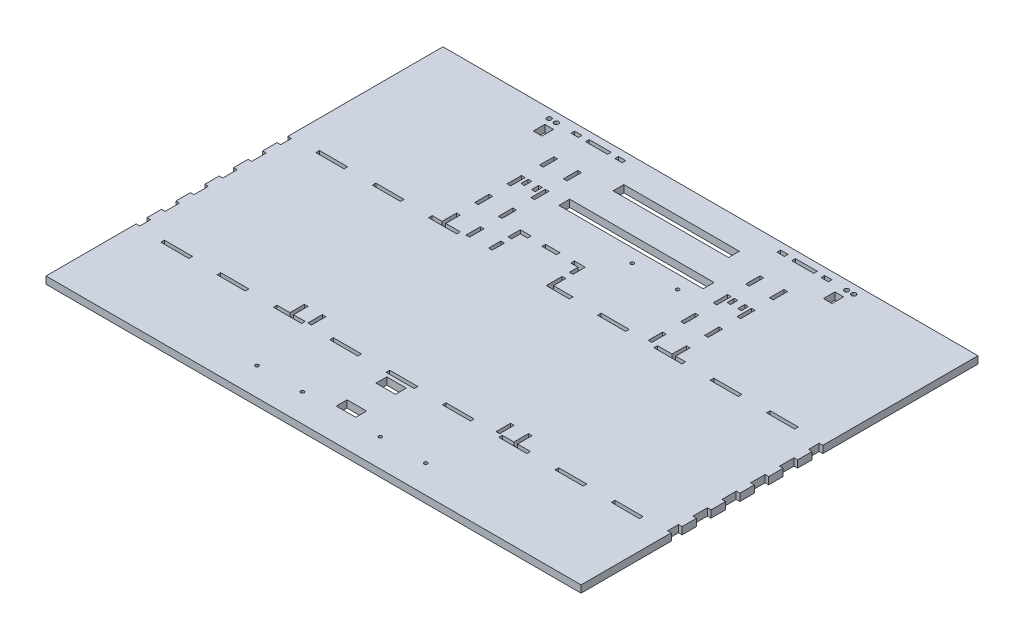
SolidWorks part; units mm, degrees
material "Acrylic (Medium-high impact)"
ref_plane "Front Plane" through (0, 0, 0) normal (0, 0, 1) x (1, 0, 0)
ref_plane "Top Plane" through (0, 0, 0) normal (0, 1, 0) x (1, 0, 0)
ref_plane "Right Plane" through (0, 0, 0) normal (1, 0, 0) x (0, 0, -1)
sketch "Sketch1" plane through (0, 0, 0) normal (0, 1, 0) x (1, 0, 0)
  line L1 (-235.3945, 69.85) -> (235.3945, 69.85)
  line L2 (-235.3945, 69.85) -> (-235.3945, -69.85)
  line L3 (-235.3945, -69.85) -> (235.3945, -69.85)
  line L4 (235.3945, 69.85) -> (235.3945, -69.85)
  point P4 (-235.3945, 0)
  point P6 (0, 69.85)
  dimension "D1" = 139.7
  dimension "D2" = 470.789
extrude "Boss-Extrude1" add sketch "Sketch1" along normal blind 6.35
sketch "Sketch2" plane through (0, 6.35, 0) normal (0, 1, 0) x (1, 0, 0)
  line L0 (235.3945, -69.85) -> (235.3945, 69.85) construction
  line L1 (-235.3945, 69.85) -> (235.3945, 69.85)
  line L2 (-235.3945, 69.85) -> (-235.3945, -69.85)
  line L3 (-235.3945, -69.85) -> (235.3945, -69.85)
  line L4 (235.3945, 69.85) -> (235.3945, -69.85)
  line L5 (-235.3945, -69.85) -> (235.3945, -69.85) construction
  line L7 (-232.2195, 66.675) -> (232.2195, 66.675)
  line L8 (-232.2195, 66.675) -> (-232.2195, -66.675)
  line L9 (-232.2195, -66.675) -> (232.2195, -66.675)
  line L10 (232.2195, 66.675) -> (232.2195, -66.675)
  point P7 (-232.2195, 0)
  point P14 (-235.3945, 0)
  point P15 (0, -66.675)
  point P16 (0, -69.85)
  point P17 (232.2195, 0)
  point P18 (235.3945, 0)
  dimension "D1" = 3.175
  dimension "D2" = 3.175
extrude "Boss-Extrude2" add sketch "Sketch2" along normal blind 298.45
sketch "Sketch3" plane through (0, 0, 69.85) normal (0, 0, 1) x (1, 0, 0)
  line L0 (73.4695, 304.8) -> (73.4695, 0) construction
  line L2 (-232.2195, 6.35) -> (232.2195, 6.35) construction
  line L4 (70.1675, 292.354) -> (70.1675, 6.35)
  line L5 (70.1675, 6.35) -> (76.7715, 6.35)
  line L6 (76.7715, 283.2407) -> (76.7715, 6.35)
  line L11 (76.7715, 101.6) -> (63.0555, 101.6) construction
  line L12 (-235.3945, 0) -> (235.3945, 0) construction
  line L13 (60.2615, 88.9) -> (60.2615, 101.6) construction
  line L14 (57.4675, 88.9) -> (63.0555, 88.9)
  line L15 (57.4675, 88.9) -> (57.4675, 71.9667)
  line L16 (57.4675, 71.9667) -> (63.0555, 71.9667)
  line L17 (63.0555, 88.9) -> (63.0555, 71.9667)
  line L18 (57.4675, 42.3333) -> (63.0555, 42.3333)
  line L19 (57.4675, 42.3333) -> (57.4675, 59.2667)
  line L20 (57.4675, 59.2667) -> (63.0555, 59.2667)
  line L21 (63.0555, 42.3333) -> (63.0555, 59.2667)
  line L26 (57.4675, 29.6333) -> (63.0555, 29.6333)
  line L27 (57.4675, 29.6333) -> (57.4675, 12.7)
  line L28 (57.4675, 12.7) -> (63.0555, 12.7)
  line L29 (63.0555, 29.6333) -> (63.0555, 12.7)
  line L30 (60.2615, 59.2667) -> (60.2615, 71.9667) construction
  line L31 (60.2615, 29.6333) -> (60.2615, 42.3333) construction
  line L32 (60.2615, 12.7) -> (60.2615, 0) construction
  line L33 (-235.3945, 304.8) -> (235.3945, 304.8) construction
  line L34 (-76.7715, 283.2407) -> (-76.7715, 6.35)
  line L35 (-76.7715, 6.35) -> (-70.1675, 6.35)
  line L36 (-70.1675, 292.354) -> (-70.1675, 6.35)
  line L37 (-70.1675, 292.354) -> (-89.7255, 292.354)
  line L38 (-79.3115, 285.7807) -> (-89.7255, 285.7807)
  line L39 (-89.7255, 292.354) -> (-89.7255, 285.7807)
  line L40 (-70.1675, 101.6) -> (-57.4675, 101.6) construction
  line L41 (-60.2615, 88.9) -> (-60.2615, 101.6) construction
  line L42 (-63.0555, 88.9) -> (-57.4675, 88.9)
  line L43 (-63.0555, 88.9) -> (-63.0555, 71.9667)
  line L44 (-63.0555, 71.9667) -> (-57.4675, 71.9667)
  line L45 (-57.4675, 88.9) -> (-57.4675, 71.9667)
  line L46 (-63.0555, 42.3333) -> (-57.4675, 42.3333)
  line L47 (-63.0555, 42.3333) -> (-63.0555, 59.2667)
  line L48 (-63.0555, 59.2667) -> (-57.4675, 59.2667)
  line L49 (-57.4675, 42.3333) -> (-57.4675, 59.2667)
  line L50 (-63.0555, 29.6333) -> (-57.4675, 29.6333)
  line L51 (-63.0555, 29.6333) -> (-63.0555, 12.7)
  line L52 (-63.0555, 12.7) -> (-57.4675, 12.7)
  line L53 (-57.4675, 29.6333) -> (-57.4675, 12.7)
  line L54 (-60.2615, 59.2667) -> (-60.2615, 71.9667) construction
  line L55 (-60.2615, 29.6333) -> (-60.2615, 42.3333) construction
  line L56 (-60.2615, 12.7) -> (-60.2615, 0) construction
  line L58 (70.1675, 292.354) -> (89.7255, 292.354)
  line L59 (89.7255, 292.354) -> (89.7255, 285.7807)
  line L60 (79.3115, 285.7807) -> (89.7255, 285.7807)
  line L61 (-235.3945, 304.8) -> (-235.3945, 0) construction
  line L62 (235.3945, 304.8) -> (235.3945, 0) construction
  arc A1 (-76.7715, 283.2407) -> (-79.3115, 285.7807) centre (-79.3115, 283.2407) ccw
  arc A2 (79.3115, 285.7807) -> (76.7715, 283.2407) centre (79.3115, 283.2407) ccw
  point P5 (73.4695, 6.35)
  dimension "D14" = 2.54
  dimension "D1" = 6.604
  dimension "D2" = 6.5733
  dimension "D3" = 158.623
  dimension "D4" = 158.623
  dimension "D6" = 101.6
  dimension "D7" = 12.7
  dimension "D8" = 12.7
  dimension "D9" = 5.588
  dimension "D11" = 6.604
  dimension "D12" = 12.954
  dimension "D13" = 286.004
  dimension "D15" = 12.7
  dimension "D16" = 12.7
  dimension "D17" = 5.588
extrude "Door Slot" cut sketch "Sketch3" against normal blind 12.7
sketch "Sketch4" plane through (0, 0, -66.675) normal (0, 0, 1) x (1, 0, 0)
  line L0 (-235.3945, 304.8) -> (235.3945, 304.8) construction
  line L1 (63.8175, 304.8) -> (70.1675, 304.8)
  line L2 (63.8175, 304.8) -> (63.8175, 6.35)
  line L3 (63.8175, 6.35) -> (70.1675, 6.35)
  line L4 (70.1675, 304.8) -> (70.1675, 6.35)
  line L5 (92.9005, 263.525) -> (92.9005, 247.65) construction
  line L7 (89.7255, 304.8) -> (96.0755, 304.8)
  line L8 (89.7255, 304.8) -> (89.7255, 6.35)
  line L9 (89.7255, 6.35) -> (96.0755, 6.35)
  line L10 (96.0755, 304.8) -> (96.0755, 6.35)
  line L11 (232.2195, 6.35) -> (-232.2195, 6.35) construction
  line L13 (70.1675, 304.8) -> (63.8175, 304.8)
  line L14 (70.1675, 304.8) -> (70.1675, 292.1)
  line L15 (70.1675, 292.1) -> (63.8175, 292.1)
  line L16 (63.8175, 304.8) -> (63.8175, 292.1)
  line L17 (70.1675, 276.225) -> (63.8175, 276.225)
  line L18 (70.1675, 276.225) -> (70.1675, 263.525)
  line L19 (70.1675, 263.525) -> (63.8175, 263.525)
  line L20 (63.8175, 276.225) -> (63.8175, 263.525)
  line L21 (63.8175, 6.35) -> (70.1675, 6.35)
  line L22 (63.8175, 6.35) -> (63.8175, 19.05)
  line L23 (63.8175, 19.05) -> (70.1675, 19.05)
  line L24 (70.1675, 6.35) -> (70.1675, 19.05)
  line L25 (63.8175, 34.925) -> (70.1675, 34.925)
  line L26 (63.8175, 34.925) -> (63.8175, 47.625)
  line L27 (63.8175, 47.625) -> (70.1675, 47.625)
  line L28 (70.1675, 34.925) -> (70.1675, 47.625)
  line L29 (63.8175, 92.075) -> (70.1675, 92.075)
  line L30 (63.8175, 92.075) -> (63.8175, 104.775)
  line L31 (63.8175, 104.775) -> (70.1675, 104.775)
  line L32 (70.1675, 92.075) -> (70.1675, 104.775)
  line L33 (63.8175, 149.225) -> (70.1675, 149.225)
  line L34 (63.8175, 149.225) -> (63.8175, 161.925)
  line L35 (63.8175, 161.925) -> (70.1675, 161.925)
  line L36 (70.1675, 149.225) -> (70.1675, 161.925)
  line L37 (63.8175, 177.8) -> (70.1675, 177.8)
  line L38 (63.8175, 177.8) -> (63.8175, 190.5)
  line L39 (63.8175, 190.5) -> (70.1675, 190.5)
  line L40 (70.1675, 177.8) -> (70.1675, 190.5)
  line L41 (63.8175, 206.375) -> (70.1675, 206.375)
  line L42 (63.8175, 206.375) -> (63.8175, 219.075)
  line L43 (63.8175, 219.075) -> (70.1675, 219.075)
  line L44 (70.1675, 206.375) -> (70.1675, 219.075)
  line L45 (63.8175, 234.95) -> (70.1675, 234.95)
  line L46 (63.8175, 234.95) -> (63.8175, 247.65)
  line L47 (63.8175, 247.65) -> (70.1675, 247.65)
  line L48 (70.1675, 234.95) -> (70.1675, 247.65)
  line L49 (70.1675, 133.35) -> (63.8175, 133.35)
  line L50 (70.1675, 133.35) -> (70.1675, 120.65)
  line L51 (70.1675, 120.65) -> (63.8175, 120.65)
  line L52 (63.8175, 133.35) -> (63.8175, 120.65)
  line L53 (70.1675, 76.2) -> (63.8175, 76.2)
  line L54 (70.1675, 76.2) -> (70.1675, 63.5)
  line L55 (70.1675, 63.5) -> (63.8175, 63.5)
  line L56 (63.8175, 76.2) -> (63.8175, 63.5)
  line L57 (66.9925, 304.8) -> (66.9925, 292.1) construction
  line L58 (66.9925, 292.1) -> (66.9925, 276.225) construction
  line L59 (66.9925, 276.225) -> (66.9925, 263.525) construction
  line L60 (66.9925, 247.65) -> (66.9925, 234.95) construction
  line L61 (66.9925, 234.95) -> (66.9925, 219.075) construction
  line L62 (66.9925, 219.075) -> (66.9925, 206.375) construction
  line L63 (66.9925, 206.375) -> (66.9925, 190.5) construction
  line L64 (66.9925, 190.5) -> (66.9925, 177.8) construction
  line L65 (66.9925, 177.8) -> (66.9925, 161.925) construction
  line L66 (66.9925, 161.925) -> (66.9925, 149.225) construction
  line L67 (66.9925, 133.35) -> (66.9925, 120.65) construction
  line L68 (66.9925, 120.65) -> (66.9925, 104.775) construction
  line L69 (66.9925, 104.775) -> (66.9925, 92.075) construction
  line L70 (66.9925, 92.075) -> (66.9925, 76.2) construction
  line L71 (66.9925, 76.2) -> (66.9925, 63.5) construction
  line L72 (66.9925, 63.5) -> (66.9925, 47.625) construction
  line L73 (66.9925, 47.625) -> (66.9925, 34.925) construction
  line L74 (66.9925, 34.925) -> (66.9925, 19.05) construction
  line L75 (66.9925, 19.05) -> (66.9925, 6.35) construction
  line L76 (66.9925, 149.225) -> (66.9925, 133.35) construction
  line L77 (66.9925, 263.525) -> (66.9925, 247.65) construction
  line L78 (79.9465, 304.8) -> (79.9465, 0) construction
  line L79 (235.3945, 304.8) -> (-235.3945, 304.8) construction
  line L80 (235.3945, 0) -> (-235.3945, 0) construction
  line L81 (79.9465, 15.1854) -> (89.7255, 15.1854) construction
  line L82 (79.9465, 15.1854) -> (70.1675, 15.1854) construction
  line L83 (92.9005, 149.225) -> (92.9005, 133.35) construction
  line L84 (92.9005, 19.05) -> (92.9005, 6.35) construction
  line L85 (92.9005, 34.925) -> (92.9005, 19.05) construction
  line L86 (92.9005, 47.625) -> (92.9005, 34.925) construction
  line L87 (92.9005, 63.5) -> (92.9005, 47.625) construction
  line L88 (92.9005, 76.2) -> (92.9005, 63.5) construction
  line L89 (92.9005, 92.075) -> (92.9005, 76.2) construction
  line L90 (92.9005, 104.775) -> (92.9005, 92.075) construction
  line L91 (92.9005, 120.65) -> (92.9005, 104.775) construction
  line L92 (92.9005, 133.35) -> (92.9005, 120.65) construction
  line L93 (92.9005, 161.925) -> (92.9005, 149.225) construction
  line L94 (92.9005, 177.8) -> (92.9005, 161.925) construction
  line L95 (92.9005, 190.5) -> (92.9005, 177.8) construction
  line L96 (92.9005, 206.375) -> (92.9005, 190.5) construction
  line L97 (92.9005, 219.075) -> (92.9005, 206.375) construction
  line L98 (92.9005, 234.95) -> (92.9005, 219.075) construction
  line L99 (92.9005, 247.65) -> (92.9005, 234.95) construction
  line L100 (92.9005, 276.225) -> (92.9005, 263.525) construction
  line L101 (92.9005, 292.1) -> (92.9005, 276.225) construction
  line L102 (92.9005, 304.8) -> (92.9005, 292.1) construction
  line L103 (96.0755, 76.2) -> (96.0755, 63.5)
  line L104 (89.7255, 63.5) -> (96.0755, 63.5)
  line L105 (89.7255, 76.2) -> (89.7255, 63.5)
  line L106 (89.7255, 76.2) -> (96.0755, 76.2)
  line L107 (96.0755, 133.35) -> (96.0755, 120.65)
  line L108 (89.7255, 120.65) -> (96.0755, 120.65)
  line L109 (89.7255, 133.35) -> (89.7255, 120.65)
  line L110 (89.7255, 133.35) -> (96.0755, 133.35)
  line L111 (89.7255, 234.95) -> (89.7255, 247.65)
  line L112 (96.0755, 247.65) -> (89.7255, 247.65)
  line L113 (96.0755, 234.95) -> (96.0755, 247.65)
  line L114 (96.0755, 234.95) -> (89.7255, 234.95)
  line L115 (89.7255, 206.375) -> (89.7255, 219.075)
  line L116 (96.0755, 219.075) -> (89.7255, 219.075)
  line L117 (96.0755, 206.375) -> (96.0755, 219.075)
  line L118 (96.0755, 206.375) -> (89.7255, 206.375)
  line L119 (89.7255, 177.8) -> (89.7255, 190.5)
  line L120 (96.0755, 190.5) -> (89.7255, 190.5)
  line L121 (96.0755, 177.8) -> (96.0755, 190.5)
  line L122 (96.0755, 177.8) -> (89.7255, 177.8)
  line L123 (89.7255, 149.225) -> (89.7255, 161.925)
  line L124 (96.0755, 161.925) -> (89.7255, 161.925)
  line L125 (96.0755, 149.225) -> (96.0755, 161.925)
  line L126 (96.0755, 149.225) -> (89.7255, 149.225)
  line L127 (89.7255, 92.075) -> (89.7255, 104.775)
  line L128 (96.0755, 104.775) -> (89.7255, 104.775)
  line L129 (96.0755, 92.075) -> (96.0755, 104.775)
  line L130 (96.0755, 92.075) -> (89.7255, 92.075)
  line L131 (89.7255, 34.925) -> (89.7255, 47.625)
  line L132 (96.0755, 47.625) -> (89.7255, 47.625)
  line L133 (96.0755, 34.925) -> (96.0755, 47.625)
  line L134 (96.0755, 34.925) -> (89.7255, 34.925)
  line L135 (89.7255, 6.35) -> (89.7255, 19.05)
  line L136 (96.0755, 19.05) -> (89.7255, 19.05)
  line L137 (96.0755, 6.35) -> (96.0755, 19.05)
  line L138 (96.0755, 6.35) -> (89.7255, 6.35)
  line L139 (96.0755, 276.225) -> (96.0755, 263.525)
  line L140 (89.7255, 263.525) -> (96.0755, 263.525)
  line L141 (89.7255, 276.225) -> (89.7255, 263.525)
  line L142 (89.7255, 276.225) -> (96.0755, 276.225)
  line L143 (96.0755, 304.8) -> (96.0755, 292.1)
  line L144 (89.7255, 292.1) -> (96.0755, 292.1)
  line L145 (89.7255, 304.8) -> (89.7255, 292.1)
  line L146 (89.7255, 304.8) -> (96.0755, 304.8)
  line L147 (89.7255, 304.8) -> (89.7255, 6.35)
  line L148 (96.0755, 6.35) -> (89.7255, 6.35)
  line L149 (96.0755, 304.8) -> (96.0755, 6.35)
  line L150 (96.0755, 304.8) -> (89.7255, 304.8)
  line L151 (-96.0755, 304.8) -> (-89.7255, 304.8)
  line L152 (-96.0755, 304.8) -> (-96.0755, 6.35)
  line L153 (-96.0755, 6.35) -> (-89.7255, 6.35)
  line L154 (-89.7255, 304.8) -> (-89.7255, 6.35)
  line L155 (-66.9925, 263.525) -> (-66.9925, 247.65) construction
  line L156 (-70.1675, 304.8) -> (-63.8175, 304.8)
  line L157 (-70.1675, 304.8) -> (-70.1675, 6.35)
  line L158 (-70.1675, 6.35) -> (-63.8175, 6.35)
  line L159 (-63.8175, 304.8) -> (-63.8175, 6.35)
  line L160 (-89.7255, 304.8) -> (-96.0755, 304.8)
  line L161 (-89.7255, 304.8) -> (-89.7255, 292.1)
  line L162 (-89.7255, 292.1) -> (-96.0755, 292.1)
  line L163 (-96.0755, 304.8) -> (-96.0755, 292.1)
  line L164 (-89.7255, 276.225) -> (-96.0755, 276.225)
  line L165 (-89.7255, 276.225) -> (-89.7255, 263.525)
  line L166 (-89.7255, 263.525) -> (-96.0755, 263.525)
  line L167 (-96.0755, 276.225) -> (-96.0755, 263.525)
  line L168 (-96.0755, 6.35) -> (-89.7255, 6.35)
  line L169 (-96.0755, 6.35) -> (-96.0755, 19.05)
  line L170 (-96.0755, 19.05) -> (-89.7255, 19.05)
  line L171 (-89.7255, 6.35) -> (-89.7255, 19.05)
  line L172 (-96.0755, 34.925) -> (-89.7255, 34.925)
  line L173 (-96.0755, 34.925) -> (-96.0755, 47.625)
  line L174 (-96.0755, 47.625) -> (-89.7255, 47.625)
  line L175 (-89.7255, 34.925) -> (-89.7255, 47.625)
  line L176 (-96.0755, 92.075) -> (-89.7255, 92.075)
  line L177 (-96.0755, 92.075) -> (-96.0755, 104.775)
  line L178 (-96.0755, 104.775) -> (-89.7255, 104.775)
  line L179 (-89.7255, 92.075) -> (-89.7255, 104.775)
  line L180 (-96.0755, 149.225) -> (-89.7255, 149.225)
  line L181 (-96.0755, 149.225) -> (-96.0755, 161.925)
  line L182 (-96.0755, 161.925) -> (-89.7255, 161.925)
  line L183 (-89.7255, 149.225) -> (-89.7255, 161.925)
  line L184 (-96.0755, 177.8) -> (-89.7255, 177.8)
  line L185 (-96.0755, 177.8) -> (-96.0755, 190.5)
  line L186 (-96.0755, 190.5) -> (-89.7255, 190.5)
  line L187 (-89.7255, 177.8) -> (-89.7255, 190.5)
  line L188 (-96.0755, 206.375) -> (-89.7255, 206.375)
  line L189 (-96.0755, 206.375) -> (-96.0755, 219.075)
  line L190 (-96.0755, 219.075) -> (-89.7255, 219.075)
  line L191 (-89.7255, 206.375) -> (-89.7255, 219.075)
  line L192 (-96.0755, 234.95) -> (-89.7255, 234.95)
  line L193 (-96.0755, 234.95) -> (-96.0755, 247.65)
  line L194 (-96.0755, 247.65) -> (-89.7255, 247.65)
  line L195 (-89.7255, 234.95) -> (-89.7255, 247.65)
  line L196 (-89.7255, 133.35) -> (-96.0755, 133.35)
  line L197 (-89.7255, 133.35) -> (-89.7255, 120.65)
  line L198 (-89.7255, 120.65) -> (-96.0755, 120.65)
  line L199 (-96.0755, 133.35) -> (-96.0755, 120.65)
  line L200 (-89.7255, 76.2) -> (-96.0755, 76.2)
  line L201 (-89.7255, 76.2) -> (-89.7255, 63.5)
  line L202 (-89.7255, 63.5) -> (-96.0755, 63.5)
  line L203 (-96.0755, 76.2) -> (-96.0755, 63.5)
  line L204 (-92.9005, 304.8) -> (-92.9005, 292.1) construction
  line L205 (-92.9005, 292.1) -> (-92.9005, 276.225) construction
  line L206 (-92.9005, 276.225) -> (-92.9005, 263.525) construction
  line L207 (-92.9005, 247.65) -> (-92.9005, 234.95) construction
  line L208 (-92.9005, 234.95) -> (-92.9005, 219.075) construction
  line L209 (-92.9005, 219.075) -> (-92.9005, 206.375) construction
  line L210 (-92.9005, 206.375) -> (-92.9005, 190.5) construction
  line L211 (-92.9005, 190.5) -> (-92.9005, 177.8) construction
  line L212 (-92.9005, 177.8) -> (-92.9005, 161.925) construction
  line L213 (-92.9005, 161.925) -> (-92.9005, 149.225) construction
  line L214 (-92.9005, 133.35) -> (-92.9005, 120.65) construction
  line L215 (-92.9005, 120.65) -> (-92.9005, 104.775) construction
  line L216 (-92.9005, 104.775) -> (-92.9005, 92.075) construction
  line L217 (-92.9005, 92.075) -> (-92.9005, 76.2) construction
  line L218 (-92.9005, 76.2) -> (-92.9005, 63.5) construction
  line L219 (-92.9005, 63.5) -> (-92.9005, 47.625) construction
  line L220 (-92.9005, 47.625) -> (-92.9005, 34.925) construction
  line L221 (-92.9005, 34.925) -> (-92.9005, 19.05) construction
  line L222 (-92.9005, 19.05) -> (-92.9005, 6.35) construction
  line L223 (-92.9005, 149.225) -> (-92.9005, 133.35) construction
  line L224 (-92.9005, 263.525) -> (-92.9005, 247.65) construction
  line L225 (-79.9465, 304.8) -> (-79.9465, 0) construction
  line L226 (-79.9465, 341.727) -> (-70.1675, 341.727) construction
  line L227 (-79.9465, 341.727) -> (-89.7255, 341.727) construction
  line L228 (-66.9925, 149.225) -> (-66.9925, 133.35) construction
  line L229 (-66.9925, 19.05) -> (-66.9925, 6.35) construction
  line L230 (-66.9925, 34.925) -> (-66.9925, 19.05) construction
  line L231 (-66.9925, 47.625) -> (-66.9925, 34.925) construction
  line L232 (-66.9925, 63.5) -> (-66.9925, 47.625) construction
  line L233 (-66.9925, 76.2) -> (-66.9925, 63.5) construction
  line L234 (-66.9925, 92.075) -> (-66.9925, 76.2) construction
  line L235 (-66.9925, 104.775) -> (-66.9925, 92.075) construction
  line L236 (-66.9925, 120.65) -> (-66.9925, 104.775) construction
  line L237 (-66.9925, 133.35) -> (-66.9925, 120.65) construction
  line L238 (-66.9925, 161.925) -> (-66.9925, 149.225) construction
  line L239 (-66.9925, 177.8) -> (-66.9925, 161.925) construction
  line L240 (-66.9925, 190.5) -> (-66.9925, 177.8) construction
  line L241 (-66.9925, 206.375) -> (-66.9925, 190.5) construction
  line L242 (-66.9925, 219.075) -> (-66.9925, 206.375) construction
  line L243 (-66.9925, 234.95) -> (-66.9925, 219.075) construction
  line L244 (-66.9925, 247.65) -> (-66.9925, 234.95) construction
  line L245 (-66.9925, 276.225) -> (-66.9925, 263.525) construction
  line L246 (-66.9925, 292.1) -> (-66.9925, 276.225) construction
  line L247 (-66.9925, 304.8) -> (-66.9925, 292.1) construction
  line L248 (-63.8175, 76.2) -> (-63.8175, 63.5)
  line L249 (-70.1675, 63.5) -> (-63.8175, 63.5)
  line L250 (-70.1675, 76.2) -> (-70.1675, 63.5)
  line L251 (-70.1675, 76.2) -> (-63.8175, 76.2)
  line L252 (-63.8175, 133.35) -> (-63.8175, 120.65)
  line L253 (-70.1675, 120.65) -> (-63.8175, 120.65)
  line L254 (-70.1675, 133.35) -> (-70.1675, 120.65)
  line L255 (-70.1675, 133.35) -> (-63.8175, 133.35)
  line L256 (-70.1675, 234.95) -> (-70.1675, 247.65)
  line L257 (-63.8175, 247.65) -> (-70.1675, 247.65)
  line L258 (-63.8175, 234.95) -> (-63.8175, 247.65)
  line L259 (-63.8175, 234.95) -> (-70.1675, 234.95)
  line L260 (-70.1675, 206.375) -> (-70.1675, 219.075)
  line L261 (-63.8175, 219.075) -> (-70.1675, 219.075)
  line L262 (-63.8175, 206.375) -> (-63.8175, 219.075)
  line L263 (-63.8175, 206.375) -> (-70.1675, 206.375)
  line L264 (-70.1675, 177.8) -> (-70.1675, 190.5)
  line L265 (-63.8175, 190.5) -> (-70.1675, 190.5)
  line L266 (-63.8175, 177.8) -> (-63.8175, 190.5)
  line L267 (-63.8175, 177.8) -> (-70.1675, 177.8)
  line L268 (-70.1675, 149.225) -> (-70.1675, 161.925)
  line L269 (-63.8175, 161.925) -> (-70.1675, 161.925)
  line L270 (-63.8175, 149.225) -> (-63.8175, 161.925)
  line L271 (-63.8175, 149.225) -> (-70.1675, 149.225)
  line L272 (-70.1675, 92.075) -> (-70.1675, 104.775)
  line L273 (-63.8175, 104.775) -> (-70.1675, 104.775)
  line L274 (-63.8175, 92.075) -> (-63.8175, 104.775)
  line L275 (-63.8175, 92.075) -> (-70.1675, 92.075)
  line L276 (-70.1675, 34.925) -> (-70.1675, 47.625)
  line L277 (-63.8175, 47.625) -> (-70.1675, 47.625)
  line L278 (-63.8175, 34.925) -> (-63.8175, 47.625)
  line L279 (-63.8175, 34.925) -> (-70.1675, 34.925)
  line L280 (-70.1675, 6.35) -> (-70.1675, 19.05)
  line L281 (-63.8175, 19.05) -> (-70.1675, 19.05)
  line L282 (-63.8175, 6.35) -> (-63.8175, 19.05)
  line L283 (-63.8175, 6.35) -> (-70.1675, 6.35)
  line L284 (-63.8175, 276.225) -> (-63.8175, 263.525)
  line L285 (-70.1675, 263.525) -> (-63.8175, 263.525)
  line L286 (-70.1675, 276.225) -> (-70.1675, 263.525)
  line L287 (-70.1675, 276.225) -> (-63.8175, 276.225)
  line L288 (-63.8175, 304.8) -> (-63.8175, 292.1)
  line L289 (-70.1675, 292.1) -> (-63.8175, 292.1)
  line L290 (-70.1675, 304.8) -> (-70.1675, 292.1)
  line L291 (-70.1675, 304.8) -> (-63.8175, 304.8)
  line L292 (-70.1675, 304.8) -> (-70.1675, 6.35)
  line L293 (-63.8175, 6.35) -> (-70.1675, 6.35)
  line L294 (-63.8175, 304.8) -> (-63.8175, 6.35)
  line L295 (-63.8175, 304.8) -> (-70.1675, 304.8)
  line L296 (-235.3945, 0) -> (235.3945, 0) construction
  line L297 (-89.7255, 292.354) -> (-89.7255, 285.7807) construction
  line L298 (-70.1675, 6.35) -> (-70.1675, 292.354) construction
  line L299 (70.1675, 292.354) -> (70.1675, 6.35) construction
  line L300 (89.7255, 285.7807) -> (89.7255, 292.354) construction
  dimension "D1" = 6.35
  dimension "D2" = 12.7
  dimension "D3" = 6.35
  dimension "D4" = 12.7
extrude "Door Guide Holes" cut sketch "Sketch4" against normal up to next (3.175 mm away) contours L2 L47 L4 L19 | L45 L2 L43 L4 | L41 L2 L39 L4 | L37 L2 L35 L4 | L49 L4 L33 L2 | L4 L51 L2 L31 | L53 L4 L29 L2 | L4 L55 L2 L27 | L25 L2 L23 L4 | L164 L154 L162 L152 | L152 L194 L154 L166 | L192 L152 L190 L154 | L188 L152 L186 L154 | L184 L152 L182 L154 | L196 L154 L180 L152 | L154 L198 L152 L178 | L200 L154 L176 L152 | L154 L202 L152 L174 | L172 L152 L170 L154 | L144 L8 L142 L10 | L140 L8 L112 L10 | L116 L10 L114 L8 | L120 L10 L118 L8 | L124 L10 L122 L8 | L10 L126 L8 L110 | L128 L10 L108 L8 | L10 L130 L8 L106 | L132 L10 L104 L8 | L136 L10 L134 L8 | L289 L157 L287 L159 | L285 L157 L257 L159 | L261 L159 L259 L157 | L265 L159 L263 L157 | L269 L159 L267 L157 | L159 L271 L157 L255 | L273 L159 L253 L157 | L159 L275 L157 L251 | L277 L159 L249 L157 | L281 L159 L279 L157 | L17 L4 L15 L2 region at (66.9925, 284.1625, -66.675) region at (66.9925, 255.5875, -66.675) region at (66.9925, 227.0125, -66.675) region at (66.9925, 198.4375, -66.675) region at (66.9925, 169.8625, -66.675) region at (66.9925, 141.2875, -66.675) region at (66.9925, 112.7125, -66.675) region at (66.9925, 84.1375, -66.675) region at (66.9925, 55.5625, -66.675) region at (66.9925, 26.9875, -66.675) region at (92.9005, 284.1625, -66.675) region at (92.9005, 255.5875, -66.675) region at (92.9005, 227.0125, -66.675) region at (92.9005, 198.4375, -66.675) region at (92.9005, 169.8625, -66.675) region at (92.9005, 141.2875, -66.675) region at (92.9005, 112.7125, -66.675) region at (92.9005, 84.1375, -66.675) region at (92.9005, 55.5625, -66.675) region at (92.9005, 26.9875, -66.675) region at (-92.9005, 284.1625, -66.675) region at (-92.9005, 255.5875, -66.675) region at (-92.9005, 227.0125, -66.675) region at (-92.9005, 198.4375, -66.675) region at (-92.9005, 169.8625, -66.675) region at (-92.9005, 141.2875, -66.675) region at (-92.9005, 112.7125, -66.675) region at (-92.9005, 84.1375, -66.675) region at (-92.9005, 55.5625, -66.675) region at (-92.9005, 26.9875, -66.675) region at (-66.9925, 284.1625, -66.675) region at (-66.9925, 255.5875, -66.675) region at (-66.9925, 227.0125, -66.675) region at (-66.9925, 198.4375, -66.675) region at (-66.9925, 169.8625, -66.675) region at (-66.9925, 141.2875, -66.675) region at (-66.9925, 112.7125, -66.675) region at (-66.9925, 84.1375, -66.675) region at (-66.9925, 55.5625, -66.675) region at (-66.9925, 26.9875, -66.675)
sketch "Lever Holes" plane through (0, 0, -69.85) normal (0, 0, 1) x (1, 0, 0)
  line L0 (-53.2675, 37.685) -> (-27.8675, 37.685)
  line L1 (-53.2675, 37.685) -> (-53.2675, 30.065)
  line L2 (-53.2675, 30.065) -> (-27.8675, 30.065)
  line L3 (-27.8675, 37.685) -> (-27.8675, 30.065)
  line L4 (-53.8175, 16.35) -> (-49.8175, 16.35)
  line L5 (-53.8175, 16.35) -> (-53.8175, 10)
  line L6 (-53.8175, 10) -> (-49.8175, 10)
  line L7 (-49.8175, 16.35) -> (-49.8175, 10)
  line L8 (-7.8175, 16.35) -> (-3.8175, 16.35)
  line L9 (-7.8175, 16.35) -> (-7.8175, 10)
  line L10 (-7.8175, 10) -> (-3.8175, 10)
  line L11 (-3.8175, 16.35) -> (-3.8175, 10)
  line L12 (-49.8175, 13.175) -> (-7.8175, 13.175) construction
  line L13 (76.7715, 6.35) -> (76.7715, 283.2407) construction
  line L14 (76.7715, 6.35) -> (232.2195, 6.35) construction
  line L15 (232.2195, 6.35) -> (-232.2195, 6.35) construction
  line L16 (216.3445, 160.275) -> (216.3445, 144.525) construction
  line L17 (235.3945, 304.8) -> (235.3945, 0) construction
  line L18 (0, -3.4925) -> (0, 3.4925) construction
  line L19 (76.7715, 154.6735) -> (-76.7715, 154.6735) construction
  line L20 (-76.7715, 283.2407) -> (-76.7715, 6.35) construction
  line L21 (0, 171.6172) -> (0, 142.0428) construction
  line L22 (7.8175, 16.35) -> (7.8175, 10)
  line L23 (7.8175, 10) -> (3.8175, 10)
  line L24 (3.8175, 16.35) -> (3.8175, 10)
  line L25 (7.8175, 16.35) -> (3.8175, 16.35)
  line L26 (53.2675, 37.685) -> (53.2675, 30.065)
  line L27 (53.2675, 30.065) -> (27.8675, 30.065)
  line L28 (27.8675, 37.685) -> (27.8675, 30.065)
  line L29 (53.2675, 37.685) -> (27.8675, 37.685)
  line L30 (53.8175, 16.35) -> (53.8175, 10)
  line L31 (53.8175, 10) -> (49.8175, 10)
  line L32 (49.8175, 16.35) -> (49.8175, 10)
  line L33 (53.8175, 16.35) -> (49.8175, 16.35)
  line L35 (63.8175, 19.05) -> (63.8175, 34.925) construction
  circle A0 centre (216.3445, 160.275) radius 1.5
  circle A1 centre (216.3445, 144.525) radius 1.5
  circle A2 centre (-216.3445, 160.275) radius 1.5
  circle A3 centre (-216.3445, 144.525) radius 1.5
  point P13 (-40.5675, 30.065)
  point P31 (216.3445, 152.4)
  point P32 (235.3945, 152.4)
  dimension "D10" = 3
  dimension "D1" = 25.4
  dimension "D2" = 7.62
  dimension "D3" = 4
  dimension "D4" = 6.35
  dimension "D5" = 42
  dimension "D6" = 31.335
  dimension "D7" = 10
  dimension "D8" = 10
  dimension "D9" = 13.25
  dimension "D11" = 15.75
  dimension "D12" = 19.05
extrude "LeverHole Cut" cut sketch "Lever Holes" along normal up to next
extrude "Lbracket Thru Holes" cut sketch "Lever Holes<2>" along normal through all contours A2 | A3 | A0 | A1 | A2 | A3 | A0 | A1 region at (216.3445, 160.275, -69.85) region at (216.3445, 144.525, -69.85) region at (-216.3445, 160.275, -69.85) region at (-216.3445, 144.525, -69.85)
sketch "Lever Holes<2>" plane through (0, 0, -69.85) normal (0, 0, 1) x (1, 0, 0) same geometry as "Lever Holes"
sketch "Sketch8" plane through (-235.3945, 0, 0) normal (-1, 0, 0) x (0, 0, 1)
  line L0 (-69.85, 0) -> (69.85, 0) construction
  circle A0 centre (0, 19.05) radius 3.175
  point P6 (0, 0)
  dimension "D1" = 6.35
  dimension "D2" = 19.05
extrude "Tether Hole" cut sketch "Sketch8" against normal through all
sketch "Sketch16" plane through (0, 0, 69.85) normal (0, 0, 1) x (1, 0, 0)
  line L0 (-235.3945, 304.8) -> (235.3945, 304.8) construction
  line L1 (57.3405, 304.8) -> (102.5525, 304.8)
  line L2 (57.3405, 304.8) -> (57.3405, 295.529)
  line L3 (57.3405, 295.529) -> (102.5525, 295.529)
  line L4 (102.5525, 304.8) -> (102.5525, 295.529)
  line L6 (47.8155, 295.529) -> (57.3405, 295.529)
  line L8 (57.3405, 295.529) -> (57.3405, 304.8)
  line L9 (57.3405, 304.8) -> (47.8155, 304.8)
  line L10 (47.8155, 295.529) -> (47.8155, 304.8)
  line L11 (102.5525, 295.529) -> (112.0775, 295.529)
  line L12 (102.5525, 295.529) -> (102.5525, 304.8)
  line L13 (102.5525, 304.8) -> (112.0775, 304.8)
  line L14 (112.0775, 295.529) -> (112.0775, 304.8)
  line L15 (89.7255, 292.354) -> (70.1675, 292.354) construction
  line L16 (-102.5525, 304.8) -> (-57.3405, 304.8)
  line L17 (-102.5525, 304.8) -> (-102.5525, 295.529)
  line L18 (-102.5525, 295.529) -> (-57.3405, 295.529)
  line L19 (-57.3405, 304.8) -> (-57.3405, 295.529)
  line L20 (-112.0775, 295.529) -> (-102.5525, 295.529)
  line L21 (-102.5525, 295.529) -> (-102.5525, 304.8)
  line L22 (-102.5525, 304.8) -> (-112.0775, 304.8)
  line L23 (-112.0775, 295.529) -> (-112.0775, 304.8)
  line L24 (-57.3405, 295.529) -> (-47.8155, 295.529)
  line L25 (-57.3405, 295.529) -> (-57.3405, 304.8)
  line L26 (-57.3405, 304.8) -> (-47.8155, 304.8)
  line L27 (-47.8155, 295.529) -> (-47.8155, 304.8)
  line L28 (-70.1675, 292.354) -> (-89.7255, 292.354) construction
  point P15 (79.9465, 292.354)
  point P16 (79.9465, 295.529)
  point P25 (-79.9465, 292.354)
  point P28 (-79.9465, 295.529)
  dimension "D1" = 45.212
  dimension "D2" = 3.175
  dimension "D3" = 9.525
  dimension "D4" = 45.212
  dimension "D5" = 9.525
extrude "Door Guide Roof Slots" cut sketch "Sketch16" against normal up to next contours L10 L6 L2 L9 | L11 L14 L13 L4 | L23 L20 L17 L22 | L24 L27 L26 L19 region at (52.578, 300.1645, 69.85) region at (107.315, 300.1645, 69.85) region at (-107.315, 300.1645, 69.85) region at (-52.578, 300.1645, 69.85)
sketch "Bottom" plane through (0, 0, 0) normal (0, -1, 0) x (1, 0, 0)
  line L0 (-232.2195, 66.675) -> (-112.0775, 66.675) construction
  line L1 (-235.3945, 69.85) -> (-210.6161, 69.85)
  line L2 (-235.3945, 69.85) -> (-235.3945, 66.675)
  line L3 (-235.3945, 66.675) -> (-210.6161, 66.675)
  line L4 (-210.6161, 69.85) -> (-210.6161, 66.675)
  line L5 (-210.6161, 69.85) -> (-185.8378, 69.85)
  line L6 (-210.6161, 69.85) -> (-210.6161, 66.675)
  line L7 (-210.6161, 66.675) -> (-185.8378, 66.675)
  line L8 (-185.8378, 69.85) -> (-185.8378, 66.675)
  line L9 (-185.8378, 69.85) -> (-161.0594, 69.85)
  line L10 (-185.8378, 69.85) -> (-185.8378, 66.675)
  line L11 (-185.8378, 66.675) -> (-161.0594, 66.675)
  line L12 (-161.0594, 69.85) -> (-161.0594, 66.675)
  line L13 (-161.0594, 69.85) -> (-136.281, 69.85)
  line L14 (-161.0594, 69.85) -> (-161.0594, 66.675)
  line L15 (-161.0594, 66.675) -> (-136.281, 66.675)
  line L16 (-136.281, 69.85) -> (-136.281, 66.675)
  line L17 (-235.3945, 69.85) -> (235.3945, 69.85) construction
  line L19 (-136.281, 69.85) -> (-111.5027, 69.85)
  line L20 (-136.281, 69.85) -> (-136.281, 66.675)
  line L21 (-136.281, 66.675) -> (-111.5027, 66.675)
  line L22 (-111.5027, 69.85) -> (-111.5027, 66.675)
  line L23 (-111.5027, 69.85) -> (-86.7243, 69.85)
  line L24 (-111.5027, 69.85) -> (-111.5027, 66.675)
  line L25 (-111.5027, 66.675) -> (-86.7243, 66.675)
  line L26 (-86.7243, 69.85) -> (-86.7243, 66.675)
  line L27 (-86.7243, 69.85) -> (-61.9459, 69.85)
  line L28 (-86.7243, 69.85) -> (-86.7243, 66.675)
  line L29 (-86.7243, 66.675) -> (-61.9459, 66.675)
  line L30 (-61.9459, 69.85) -> (-61.9459, 66.675)
  line L31 (-61.9459, 69.85) -> (-37.1676, 69.85)
  line L32 (-61.9459, 69.85) -> (-61.9459, 66.675)
  line L33 (-61.9459, 66.675) -> (-37.1676, 66.675)
  line L34 (-37.1676, 69.85) -> (-37.1676, 66.675)
  line L36 (-37.1676, 69.85) -> (-12.3892, 69.85)
  line L37 (-37.1676, 69.85) -> (-37.1676, 66.675)
  line L38 (-37.1676, 66.675) -> (-12.3892, 66.675)
  line L39 (-12.3892, 69.85) -> (-12.3892, 66.675)
  line L40 (-12.3892, 69.85) -> (12.3892, 69.85)
  line L41 (-12.3892, 69.85) -> (-12.3892, 66.675)
  line L42 (-12.3892, 66.675) -> (12.3892, 66.675)
  line L43 (12.3892, 69.85) -> (12.3892, 66.675)
  line L44 (12.3892, 69.85) -> (37.1676, 69.85)
  line L45 (12.3892, 69.85) -> (12.3892, 66.675)
  line L46 (12.3892, 66.675) -> (37.1676, 66.675)
  line L47 (37.1676, 69.85) -> (37.1676, 66.675)
  line L48 (37.1676, 69.85) -> (61.9459, 69.85)
  line L49 (37.1676, 69.85) -> (37.1676, 66.675)
  line L50 (37.1676, 66.675) -> (61.9459, 66.675)
  line L51 (61.9459, 69.85) -> (61.9459, 66.675)
  line L52 (61.9459, 69.85) -> (86.7243, 69.85)
  line L53 (61.9459, 69.85) -> (61.9459, 66.675)
  line L54 (61.9459, 66.675) -> (86.7243, 66.675)
  line L55 (86.7243, 69.85) -> (86.7243, 66.675)
  line L56 (86.7243, 69.85) -> (111.5027, 69.85)
  line L57 (86.7243, 69.85) -> (86.7243, 66.675)
  line L58 (86.7243, 66.675) -> (111.5027, 66.675)
  line L59 (111.5027, 69.85) -> (111.5027, 66.675)
  line L60 (111.5027, 69.85) -> (136.281, 69.85)
  line L61 (111.5027, 69.85) -> (111.5027, 66.675)
  line L62 (111.5027, 66.675) -> (136.281, 66.675)
  line L63 (136.281, 69.85) -> (136.281, 66.675)
  line L64 (136.281, 69.85) -> (161.0594, 69.85)
  line L65 (136.281, 69.85) -> (136.281, 66.675)
  line L66 (136.281, 66.675) -> (161.0594, 66.675)
  line L67 (161.0594, 69.85) -> (161.0594, 66.675)
  line L68 (161.0594, 69.85) -> (185.8378, 69.85)
  line L69 (161.0594, 69.85) -> (161.0594, 66.675)
  line L70 (161.0594, 66.675) -> (185.8378, 66.675)
  line L71 (185.8378, 69.85) -> (185.8378, 66.675)
  line L72 (185.8378, 69.85) -> (210.6161, 69.85)
  line L73 (185.8378, 69.85) -> (185.8378, 66.675)
  line L74 (185.8378, 66.675) -> (210.6161, 66.675)
  line L75 (210.6161, 69.85) -> (210.6161, 66.675)
  line L76 (-232.2195, -66.675) -> (-232.2195, 66.675) construction
  line L77 (-235.3945, 69.85) -> (-232.2195, 69.85)
  line L78 (-235.3945, 69.85) -> (-235.3945, 57.15)
  line L79 (-235.3945, 57.15) -> (-232.2195, 57.15)
  line L80 (-232.2195, 69.85) -> (-232.2195, 57.15)
  line L82 (-235.3945, 57.15) -> (-232.2195, 57.15)
  line L83 (-235.3945, 57.15) -> (-235.3945, 44.45)
  line L84 (-235.3945, 44.45) -> (-232.2195, 44.45)
  line L85 (-232.2195, 57.15) -> (-232.2195, 44.45)
  line L86 (-235.3945, 44.45) -> (-232.2195, 44.45)
  line L87 (-235.3945, 44.45) -> (-235.3945, 31.75)
  line L88 (-235.3945, 31.75) -> (-232.2195, 31.75)
  line L89 (-232.2195, 44.45) -> (-232.2195, 31.75)
  line L90 (-235.3945, 31.75) -> (-232.2195, 31.75)
  line L91 (-235.3945, 31.75) -> (-235.3945, 19.05)
  line L92 (-235.3945, 19.05) -> (-232.2195, 19.05)
  line L93 (-232.2195, 31.75) -> (-232.2195, 19.05)
  line L94 (-235.3945, 19.05) -> (-232.2195, 19.05)
  line L95 (-235.3945, 19.05) -> (-235.3945, 6.35)
  line L96 (-235.3945, 6.35) -> (-232.2195, 6.35)
  line L97 (-232.2195, 19.05) -> (-232.2195, 6.35)
  line L98 (-235.3945, 6.35) -> (-232.2195, 6.35)
  line L99 (-235.3945, 6.35) -> (-235.3945, -6.35)
  line L100 (-235.3945, -6.35) -> (-232.2195, -6.35)
  line L101 (-232.2195, 6.35) -> (-232.2195, -6.35)
  line L102 (-235.3945, -6.35) -> (-232.2195, -6.35)
  line L103 (-235.3945, -6.35) -> (-235.3945, -19.05)
  line L104 (-235.3945, -19.05) -> (-232.2195, -19.05)
  line L105 (-232.2195, -6.35) -> (-232.2195, -19.05)
  line L106 (-235.3945, -19.05) -> (-232.2195, -19.05)
  line L107 (-235.3945, -19.05) -> (-235.3945, -31.75)
  line L108 (-235.3945, -31.75) -> (-232.2195, -31.75)
  line L109 (-232.2195, -19.05) -> (-232.2195, -31.75)
  line L110 (-235.3945, -31.75) -> (-232.2195, -31.75)
  line L111 (-235.3945, -31.75) -> (-235.3945, -44.45)
  line L112 (-235.3945, -44.45) -> (-232.2195, -44.45)
  line L113 (-232.2195, -31.75) -> (-232.2195, -44.45)
  line L114 (-235.3945, -44.45) -> (-232.2195, -44.45)
  line L115 (-235.3945, -44.45) -> (-235.3945, -57.15)
  line L116 (-235.3945, -57.15) -> (-232.2195, -57.15)
  line L117 (-232.2195, -44.45) -> (-232.2195, -57.15)
  line L118 (235.3945, 69.85) -> (235.3945, -69.85) construction
  line L119 (210.6161, 69.85) -> (235.3945, 69.85)
  line L120 (210.6161, 69.85) -> (210.6161, 66.675)
  line L121 (210.6161, 66.675) -> (235.3945, 66.675)
  line L122 (235.3945, 69.85) -> (235.3945, 66.675)
  line L123 (235.3945, -69.85) -> (-235.3945, -69.85) construction
  line L124 (-235.3945, -57.15) -> (-232.2195, -57.15)
  line L125 (-235.3945, -57.15) -> (-235.3945, -69.85)
  line L126 (-235.3945, -69.85) -> (-232.2195, -69.85)
  line L127 (-232.2195, -57.15) -> (-232.2195, -69.85)
  line L128 (3.4925, 0) -> (-3.4925, 0) construction
  line L129 (235.3945, -69.85) -> (235.3945, -66.675)
  line L130 (210.6161, -66.675) -> (235.3945, -66.675)
  line L131 (210.6161, -69.85) -> (235.3945, -69.85)
  line L132 (210.6161, -69.85) -> (210.6161, -66.675)
  line L133 (185.8378, -66.675) -> (210.6161, -66.675)
  line L134 (185.8378, -69.85) -> (210.6161, -69.85)
  line L135 (185.8378, -69.85) -> (185.8378, -66.675)
  line L136 (161.0594, -66.675) -> (185.8378, -66.675)
  line L137 (161.0594, -69.85) -> (185.8378, -69.85)
  line L138 (161.0594, -69.85) -> (161.0594, -66.675)
  line L139 (136.281, -66.675) -> (161.0594, -66.675)
  line L140 (136.281, -69.85) -> (161.0594, -69.85)
  line L141 (136.281, -69.85) -> (136.281, -66.675)
  line L142 (111.5027, -66.675) -> (136.281, -66.675)
  line L143 (111.5027, -69.85) -> (136.281, -69.85)
  line L144 (86.7243, -66.675) -> (111.5027, -66.675)
  line L145 (111.5027, -69.85) -> (111.5027, -66.675)
  line L146 (86.7243, -69.85) -> (111.5027, -69.85)
  line L147 (86.7243, -69.85) -> (86.7243, -66.675)
  line L148 (61.9459, -66.675) -> (86.7243, -66.675)
  line L149 (61.9459, -69.85) -> (86.7243, -69.85)
  line L150 (61.9459, -69.85) -> (61.9459, -66.675)
  line L151 (37.1676, -66.675) -> (61.9459, -66.675)
  line L152 (37.1676, -69.85) -> (61.9459, -69.85)
  line L153 (37.1676, -69.85) -> (37.1676, -66.675)
  line L154 (12.3892, -69.85) -> (37.1676, -69.85)
  line L155 (12.3892, -66.675) -> (37.1676, -66.675)
  line L156 (12.3892, -69.85) -> (12.3892, -66.675)
  line L157 (-12.3892, -66.675) -> (12.3892, -66.675)
  line L158 (-12.3892, -69.85) -> (12.3892, -69.85)
  line L159 (-37.1676, -66.675) -> (-12.3892, -66.675)
  line L160 (-12.3892, -69.85) -> (-12.3892, -66.675)
  line L161 (-37.1676, -69.85) -> (-12.3892, -69.85)
  line L162 (-37.1676, -69.85) -> (-37.1676, -66.675)
  line L163 (-61.9459, -66.675) -> (-37.1676, -66.675)
  line L164 (-61.9459, -69.85) -> (-37.1676, -69.85)
  line L165 (-61.9459, -69.85) -> (-61.9459, -66.675)
  line L166 (-86.7243, -66.675) -> (-61.9459, -66.675)
  line L167 (-86.7243, -69.85) -> (-61.9459, -69.85)
  line L168 (-86.7243, -69.85) -> (-86.7243, -66.675)
  line L169 (-111.5027, -69.85) -> (-86.7243, -69.85)
  line L170 (-111.5027, -66.675) -> (-86.7243, -66.675)
  line L171 (-136.281, -66.675) -> (-111.5027, -66.675)
  line L172 (-111.5027, -69.85) -> (-111.5027, -66.675)
  line L173 (-136.281, -69.85) -> (-111.5027, -69.85)
  line L174 (-161.0594, -69.85) -> (-136.281, -69.85)
  line L175 (-161.0594, -66.675) -> (-136.281, -66.675)
  line L176 (-136.281, -69.85) -> (-136.281, -66.675)
  line L177 (-185.8378, -69.85) -> (-185.8378, -66.675)
  line L178 (-185.8378, -69.85) -> (-161.0594, -69.85)
  line L179 (-161.0594, -69.85) -> (-161.0594, -66.675)
  line L180 (-185.8378, -66.675) -> (-161.0594, -66.675)
  line L181 (-210.6161, -66.675) -> (-185.8378, -66.675)
  line L182 (-210.6161, -69.85) -> (-185.8378, -69.85)
  line L183 (-210.6161, -69.85) -> (-210.6161, -66.675)
  line L184 (-235.3945, -69.85) -> (-210.6161, -69.85)
  line L185 (-235.3945, -69.85) -> (-235.3945, -66.675)
  line L186 (-235.3945, -66.675) -> (-210.6161, -66.675)
  line L187 (0, -3.4925) -> (0, 3.4925) construction
  line L188 (235.3945, -69.85) -> (232.2195, -69.85)
  line L189 (232.2195, -57.15) -> (232.2195, -69.85)
  line L190 (235.3945, -57.15) -> (235.3945, -69.85)
  line L191 (235.3945, -57.15) -> (232.2195, -57.15)
  line L192 (232.2195, -44.45) -> (232.2195, -57.15)
  line L193 (235.3945, -44.45) -> (235.3945, -57.15)
  line L194 (235.3945, -44.45) -> (232.2195, -44.45)
  line L195 (232.2195, -31.75) -> (232.2195, -44.45)
  line L196 (235.3945, -31.75) -> (235.3945, -44.45)
  line L197 (235.3945, -31.75) -> (232.2195, -31.75)
  line L198 (235.3945, -19.05) -> (235.3945, -31.75)
  line L199 (232.2195, -19.05) -> (232.2195, -31.75)
  line L200 (232.2195, -6.35) -> (232.2195, -19.05)
  line L201 (235.3945, -6.35) -> (235.3945, -19.05)
  line L202 (235.3945, -19.05) -> (232.2195, -19.05)
  line L203 (235.3945, -6.35) -> (232.2195, -6.35)
  line L204 (232.2195, 6.35) -> (232.2195, -6.35)
  line L205 (235.3945, 6.35) -> (235.3945, -6.35)
  line L206 (235.3945, 6.35) -> (232.2195, 6.35)
  line L207 (232.2195, 19.05) -> (232.2195, 6.35)
  line L208 (235.3945, 19.05) -> (235.3945, 6.35)
  line L209 (235.3945, 19.05) -> (232.2195, 19.05)
  line L210 (235.3945, 31.75) -> (232.2195, 31.75)
  line L211 (235.3945, 44.45) -> (232.2195, 44.45)
  line L212 (235.3945, 57.15) -> (232.2195, 57.15)
  line L213 (232.2195, 31.75) -> (232.2195, 19.05)
  line L214 (235.3945, 31.75) -> (235.3945, 19.05)
  line L215 (232.2195, 44.45) -> (232.2195, 31.75)
  line L216 (235.3945, 44.45) -> (235.3945, 31.75)
  line L217 (232.2195, 57.15) -> (232.2195, 44.45)
  line L218 (235.3945, 57.15) -> (235.3945, 44.45)
  line L219 (232.2195, 69.85) -> (232.2195, 57.15)
  line L220 (235.3945, 69.85) -> (235.3945, 57.15)
  line M28 (-235.3945, 69.85) -> (-235.3945, -69.85)
  line M29 (-235.3945, -69.85) -> (235.3945, -69.85)
  line M30 (235.3945, -69.85) -> (235.3945, 69.85)
  line M31 (235.3945, 69.85) -> (-235.3945, 69.85)
sketch "Front/Back" plane through (0, 0, 69.85) normal (0, 0, 1) x (1, 0, 0)
  line L0 (-232.2195, 6.35) -> (-76.7715, 6.35) construction
  line L1 (-235.3945, 0) -> (-210.6161, 0)
  line L2 (-235.3945, 0) -> (-235.3945, 6.35)
  line L3 (-235.3945, 6.35) -> (-210.6161, 6.35)
  line L4 (-210.6161, 0) -> (-210.6161, 6.35)
  line L5 (-235.3945, 0) -> (235.3945, 0) construction
  line L6 (-185.8378, 0) -> (-161.0594, 0) construction
  line L7 (-210.6161, 6.35) -> (-185.8378, 6.35)
  line L8 (-210.6161, 6.35) -> (-210.6161, 0)
  line L9 (-210.6161, 0) -> (-185.8378, 0)
  line L10 (-185.8378, 6.35) -> (-185.8378, 0)
  line L11 (-136.281, 0) -> (-111.5027, 0) construction
  line L12 (-185.8378, 6.35) -> (-161.0594, 6.35)
  line L13 (-185.8378, 6.35) -> (-185.8378, 0)
  line L14 (-185.8378, 0) -> (-161.0594, 0)
  line L15 (-161.0594, 6.35) -> (-161.0594, 0)
  line L16 (-161.0594, 6.35) -> (-136.281, 6.35)
  line L17 (-161.0594, 6.35) -> (-161.0594, 0)
  line L18 (-161.0594, 0) -> (-136.281, 0)
  line L19 (-136.281, 6.35) -> (-136.281, 0)
  line L20 (-111.5027, 0) -> (-86.7243, 0) construction
  line L21 (-136.281, 6.35) -> (-111.5027, 6.35)
  line L22 (-136.281, 6.35) -> (-136.281, 0)
  line L23 (-136.281, 0) -> (-111.5027, 0)
  line L24 (-111.5027, 6.35) -> (-111.5027, 0)
  line L25 (-111.5027, 6.35) -> (-86.7243, 6.35)
  line L26 (-111.5027, 6.35) -> (-111.5027, 0)
  line L27 (-111.5027, 0) -> (-86.7243, 0)
  line L28 (-86.7243, 6.35) -> (-86.7243, 0)
  line L29 (-86.7243, 0) -> (-61.9459, 0) construction
  line L30 (-86.7243, 6.35) -> (-61.9459, 6.35)
  line L31 (-86.7243, 6.35) -> (-86.7243, 0)
  line L32 (-86.7243, 0) -> (-61.9459, 0)
  line L33 (-61.9459, 6.35) -> (-61.9459, 0)
  line L34 (-37.1676, 0) -> (-12.3892, 0) construction
  line L35 (-61.9459, 6.35) -> (-37.1676, 6.35)
  line L36 (-61.9459, 6.35) -> (-61.9459, 0)
  line L37 (-61.9459, 0) -> (-37.1676, 0)
  line L38 (-37.1676, 6.35) -> (-37.1676, 0)
  line L39 (12.3892, 0) -> (37.1676, 0) construction
  line L40 (-37.1676, 6.35) -> (-12.3892, 6.35)
  line L41 (-37.1676, 6.35) -> (-37.1676, 0)
  line L42 (-37.1676, 0) -> (-12.3892, 0)
  line L43 (-12.3892, 6.35) -> (-12.3892, 0)
  line L44 (-12.3892, 6.35) -> (12.3892, 6.35)
  line L45 (-12.3892, 6.35) -> (-12.3892, 0)
  line L46 (-12.3892, 0) -> (12.3892, 0)
  line L47 (12.3892, 6.35) -> (12.3892, 0)
  line L48 (12.3892, 0) -> (37.1676, 0) construction
  line L49 (61.9459, 0) -> (86.7243, 0) construction
  line L50 (12.3892, 6.35) -> (37.1676, 6.35)
  line L51 (12.3892, 6.35) -> (12.3892, 0)
  line L52 (12.3892, 0) -> (37.1676, 0)
  line L53 (37.1676, 6.35) -> (37.1676, 0)
  line L54 (37.1676, 6.35) -> (61.9459, 6.35)
  line L55 (37.1676, 6.35) -> (37.1676, 0)
  line L56 (37.1676, 0) -> (61.9459, 0)
  line L57 (61.9459, 6.35) -> (61.9459, 0)
  line L58 (111.5027, 0) -> (136.281, 0) construction
  line L59 (61.9459, 6.35) -> (86.7243, 6.35)
  line L60 (61.9459, 6.35) -> (61.9459, 0)
  line L61 (61.9459, 0) -> (86.7243, 0)
  line L62 (86.7243, 6.35) -> (86.7243, 0)
  line L63 (86.7243, 6.35) -> (111.5027, 6.35)
  line L64 (86.7243, 6.35) -> (86.7243, 0)
  line L65 (86.7243, 0) -> (111.5027, 0)
  line L66 (111.5027, 6.35) -> (111.5027, 0)
  line L67 (86.7243, 0) -> (111.5027, 0) construction
  line L68 (161.0594, 0) -> (185.8378, 0) construction
  line L69 (111.5027, 6.35) -> (136.281, 6.35)
  line L70 (111.5027, 6.35) -> (111.5027, 0)
  line L71 (111.5027, 0) -> (136.281, 0)
  line L72 (136.281, 6.35) -> (136.281, 0)
  line L73 (136.281, 6.35) -> (161.0594, 6.35)
  line L74 (136.281, 6.35) -> (136.281, 0)
  line L75 (136.281, 0) -> (161.0594, 0)
  line L76 (161.0594, 6.35) -> (161.0594, 0)
  line L77 (185.8378, 0) -> (210.6161, 0) construction
  line L78 (161.0594, 6.35) -> (185.8378, 6.35)
  line L79 (161.0594, 6.35) -> (161.0594, 0)
  line L80 (161.0594, 0) -> (185.8378, 0)
  line L81 (185.8378, 6.35) -> (185.8378, 0)
  line L82 (185.8378, 0) -> (210.6161, 0) construction
  line L84 (185.8378, 6.35) -> (210.6161, 6.35)
  line L85 (185.8378, 6.35) -> (185.8378, 0)
  line L86 (185.8378, 0) -> (210.6161, 0)
  line L87 (210.6161, 6.35) -> (210.6161, 0)
  line L88 (210.6161, 6.35) -> (235.3945, 6.35)
  line L89 (210.6161, 6.35) -> (210.6161, 0)
  line L90 (210.6161, 0) -> (235.3945, 0)
  line L91 (235.3945, 6.35) -> (235.3945, 0)
  line L92 (-232.2195, 304.8) -> (-232.2195, 6.35) construction
  line L93 (-235.3945, 0) -> (-232.2195, 0)
  line L94 (-235.3945, 0) -> (-235.3945, 12.7)
  line L95 (-235.3945, 12.7) -> (-232.2195, 12.7)
  line L96 (-232.2195, 0) -> (-232.2195, 12.7)
  line L97 (-235.3945, 304.8) -> (-235.3945, 0) construction
  line L98 (-235.3945, 12.7) -> (-232.2195, 12.7)
  line L99 (-235.3945, 12.7) -> (-235.3945, 25.4)
  line L100 (-235.3945, 25.4) -> (-232.2195, 25.4)
  line L101 (-232.2195, 12.7) -> (-232.2195, 25.4)
  line L102 (-235.3945, 25.4) -> (-232.2195, 25.4)
  line L103 (-235.3945, 25.4) -> (-235.3945, 38.1)
  line L104 (-235.3945, 38.1) -> (-232.2195, 38.1)
  line L105 (-232.2195, 25.4) -> (-232.2195, 38.1)
  line L106 (-235.3945, 38.1) -> (-232.2195, 38.1)
  line L107 (-235.3945, 38.1) -> (-235.3945, 50.8)
  line L108 (-235.3945, 50.8) -> (-232.2195, 50.8)
  line L109 (-232.2195, 38.1) -> (-232.2195, 50.8)
  line L110 (-235.3945, 50.8) -> (-232.2195, 50.8)
  line L111 (-235.3945, 50.8) -> (-235.3945, 63.5)
  line L112 (-235.3945, 63.5) -> (-232.2195, 63.5)
  line L113 (-232.2195, 50.8) -> (-232.2195, 63.5)
  line L114 (-235.3945, 63.5) -> (-232.2195, 63.5)
  line L115 (-235.3945, 63.5) -> (-235.3945, 76.2)
  line L116 (-235.3945, 76.2) -> (-232.2195, 76.2)
  line L117 (-232.2195, 63.5) -> (-232.2195, 76.2)
  line L118 (-235.3945, 76.2) -> (-232.2195, 76.2)
  line L119 (-235.3945, 76.2) -> (-235.3945, 88.9)
  line L120 (-235.3945, 88.9) -> (-232.2195, 88.9)
  line L121 (-232.2195, 76.2) -> (-232.2195, 88.9)
  line L122 (-235.3945, 88.9) -> (-232.2195, 88.9)
  line L123 (-235.3945, 88.9) -> (-235.3945, 101.6)
  line L124 (-235.3945, 101.6) -> (-232.2195, 101.6)
  line L125 (-232.2195, 88.9) -> (-232.2195, 101.6)
  line L126 (-235.3945, 101.6) -> (-232.2195, 101.6)
  line L127 (-235.3945, 101.6) -> (-235.3945, 114.3)
  line L128 (-235.3945, 114.3) -> (-232.2195, 114.3)
  line L129 (-232.2195, 101.6) -> (-232.2195, 114.3)
  line L130 (-235.3945, 114.3) -> (-232.2195, 114.3)
  line L131 (-235.3945, 114.3) -> (-235.3945, 127)
  line L132 (-235.3945, 127) -> (-232.2195, 127)
  line L133 (-232.2195, 114.3) -> (-232.2195, 127)
  line L134 (-235.3945, 127) -> (-232.2195, 127)
  line L135 (-235.3945, 127) -> (-235.3945, 139.7)
  line L136 (-235.3945, 139.7) -> (-232.2195, 139.7)
  line L137 (-232.2195, 127) -> (-232.2195, 139.7)
  line L138 (-235.3945, 139.7) -> (-232.2195, 139.7)
  line L139 (-235.3945, 139.7) -> (-235.3945, 152.4)
  line L140 (-235.3945, 152.4) -> (-232.2195, 152.4)
  line L141 (-232.2195, 139.7) -> (-232.2195, 152.4)
  line L142 (-235.3945, 152.4) -> (-232.2195, 152.4)
  line L143 (-235.3945, 152.4) -> (-235.3945, 165.1)
  line L144 (-235.3945, 165.1) -> (-232.2195, 165.1)
  line L145 (-232.2195, 152.4) -> (-232.2195, 165.1)
  line L146 (-235.3945, 165.1) -> (-232.2195, 165.1)
  line L147 (-235.3945, 165.1) -> (-235.3945, 177.8)
  line L148 (-235.3945, 177.8) -> (-232.2195, 177.8)
  line L149 (-232.2195, 165.1) -> (-232.2195, 177.8)
  line L150 (-235.3945, 177.8) -> (-232.2195, 177.8)
  line L151 (-235.3945, 177.8) -> (-235.3945, 190.5)
  line L152 (-235.3945, 190.5) -> (-232.2195, 190.5)
  line L153 (-232.2195, 177.8) -> (-232.2195, 190.5)
  line L154 (-235.3945, 190.5) -> (-232.2195, 190.5)
  line L155 (-235.3945, 190.5) -> (-235.3945, 203.2)
  line L156 (-235.3945, 203.2) -> (-232.2195, 203.2)
  line L157 (-232.2195, 190.5) -> (-232.2195, 203.2)
  line L158 (-235.3945, 203.2) -> (-232.2195, 203.2)
  line L159 (-235.3945, 203.2) -> (-235.3945, 215.9)
  line L160 (-235.3945, 215.9) -> (-232.2195, 215.9)
  line L161 (-232.2195, 203.2) -> (-232.2195, 215.9)
  line L162 (-235.3945, 215.9) -> (-232.2195, 215.9)
  line L163 (-235.3945, 215.9) -> (-235.3945, 228.6)
  line L164 (-235.3945, 228.6) -> (-232.2195, 228.6)
  line L165 (-232.2195, 215.9) -> (-232.2195, 228.6)
  line L166 (-235.3945, 228.6) -> (-232.2195, 228.6)
  line L167 (-235.3945, 228.6) -> (-235.3945, 241.3)
  line L168 (-235.3945, 241.3) -> (-232.2195, 241.3)
  line L169 (-232.2195, 228.6) -> (-232.2195, 241.3)
  line L170 (-235.3945, 241.3) -> (-232.2195, 241.3)
  line L171 (-235.3945, 241.3) -> (-235.3945, 254)
  line L172 (-235.3945, 254) -> (-232.2195, 254)
  line L173 (-232.2195, 241.3) -> (-232.2195, 254)
  line L174 (-235.3945, 254) -> (-232.2195, 254)
  line L175 (-235.3945, 254) -> (-235.3945, 266.7)
  line L176 (-235.3945, 266.7) -> (-232.2195, 266.7)
  line L177 (-232.2195, 254) -> (-232.2195, 266.7)
  line L178 (-235.3945, 266.7) -> (-232.2195, 266.7)
  line L179 (-235.3945, 266.7) -> (-235.3945, 279.4)
  line L180 (-235.3945, 279.4) -> (-232.2195, 279.4)
  line L181 (-232.2195, 266.7) -> (-232.2195, 279.4)
  line L182 (-235.3945, 279.4) -> (-232.2195, 279.4)
  line L183 (-235.3945, 279.4) -> (-235.3945, 292.1)
  line L184 (-235.3945, 292.1) -> (-232.2195, 292.1)
  line L185 (-232.2195, 279.4) -> (-232.2195, 292.1)
  line L186 (-235.3945, 292.1) -> (-232.2195, 292.1)
  line L187 (-235.3945, 292.1) -> (-235.3945, 304.8)
  line L188 (-235.3945, 304.8) -> (-232.2195, 304.8)
  line L189 (-232.2195, 292.1) -> (-232.2195, 304.8)
  line L190 (-235.3945, 304.8) -> (-232.2195, 304.8)
  line L194 (-235.3945, 304.8) -> (-112.0775, 304.8) construction
  line L195 (0, -3.4925) -> (0, 3.4925) construction
  line L196 (235.3945, 304.8) -> (232.2195, 304.8)
  line L197 (232.2195, 292.1) -> (232.2195, 304.8)
  line L198 (235.3945, 304.8) -> (232.2195, 304.8)
  line L199 (235.3945, 292.1) -> (235.3945, 304.8)
  line L200 (235.3945, 292.1) -> (232.2195, 292.1)
  line L201 (232.2195, 279.4) -> (232.2195, 292.1)
  line L202 (235.3945, 292.1) -> (232.2195, 292.1)
  line L203 (235.3945, 279.4) -> (235.3945, 292.1)
  line L204 (235.3945, 279.4) -> (232.2195, 279.4)
  line L205 (232.2195, 266.7) -> (232.2195, 279.4)
  line L206 (235.3945, 279.4) -> (232.2195, 279.4)
  line L207 (235.3945, 266.7) -> (235.3945, 279.4)
  line L208 (235.3945, 266.7) -> (232.2195, 266.7)
  line L209 (232.2195, 254) -> (232.2195, 266.7)
  line L210 (235.3945, 266.7) -> (232.2195, 266.7)
  line L211 (235.3945, 254) -> (235.3945, 266.7)
  line L212 (235.3945, 254) -> (232.2195, 254)
  line L213 (232.2195, 241.3) -> (232.2195, 254)
  line L214 (235.3945, 254) -> (232.2195, 254)
  line L215 (235.3945, 241.3) -> (235.3945, 254)
  line L216 (235.3945, 241.3) -> (232.2195, 241.3)
  line L217 (232.2195, 228.6) -> (232.2195, 241.3)
  line L218 (235.3945, 241.3) -> (232.2195, 241.3)
  line L219 (235.3945, 228.6) -> (235.3945, 241.3)
  line L220 (235.3945, 228.6) -> (232.2195, 228.6)
  line L221 (232.2195, 215.9) -> (232.2195, 228.6)
  line L222 (235.3945, 228.6) -> (232.2195, 228.6)
  line L223 (235.3945, 215.9) -> (235.3945, 228.6)
  line L224 (235.3945, 215.9) -> (232.2195, 215.9)
  line L225 (232.2195, 203.2) -> (232.2195, 215.9)
  line L226 (235.3945, 215.9) -> (232.2195, 215.9)
  line L227 (235.3945, 203.2) -> (235.3945, 215.9)
  line L228 (235.3945, 203.2) -> (232.2195, 203.2)
  line L229 (232.2195, 190.5) -> (232.2195, 203.2)
  line L230 (235.3945, 203.2) -> (232.2195, 203.2)
  line L231 (235.3945, 190.5) -> (235.3945, 203.2)
  line L232 (235.3945, 190.5) -> (232.2195, 190.5)
  line L233 (232.2195, 177.8) -> (232.2195, 190.5)
  line L234 (235.3945, 190.5) -> (232.2195, 190.5)
  line L235 (235.3945, 177.8) -> (235.3945, 190.5)
  line L236 (235.3945, 177.8) -> (232.2195, 177.8)
  line L237 (232.2195, 165.1) -> (232.2195, 177.8)
  line L238 (235.3945, 177.8) -> (232.2195, 177.8)
  line L239 (235.3945, 165.1) -> (235.3945, 177.8)
  line L240 (235.3945, 165.1) -> (232.2195, 165.1)
  line L241 (232.2195, 152.4) -> (232.2195, 165.1)
  line L242 (235.3945, 165.1) -> (232.2195, 165.1)
  line L243 (235.3945, 152.4) -> (235.3945, 165.1)
  line L244 (235.3945, 152.4) -> (232.2195, 152.4)
  line L245 (232.2195, 139.7) -> (232.2195, 152.4)
  line L246 (235.3945, 152.4) -> (232.2195, 152.4)
  line L247 (235.3945, 139.7) -> (235.3945, 152.4)
  line L248 (235.3945, 139.7) -> (232.2195, 139.7)
  line L249 (232.2195, 127) -> (232.2195, 139.7)
  line L250 (235.3945, 139.7) -> (232.2195, 139.7)
  line L251 (235.3945, 127) -> (235.3945, 139.7)
  line L252 (235.3945, 127) -> (232.2195, 127)
  line L253 (232.2195, 114.3) -> (232.2195, 127)
  line L254 (235.3945, 127) -> (232.2195, 127)
  line L255 (235.3945, 114.3) -> (235.3945, 127)
  line L256 (235.3945, 114.3) -> (232.2195, 114.3)
  line L257 (232.2195, 101.6) -> (232.2195, 114.3)
  line L258 (235.3945, 114.3) -> (232.2195, 114.3)
  line L259 (235.3945, 101.6) -> (235.3945, 114.3)
  line L260 (235.3945, 101.6) -> (232.2195, 101.6)
  line L261 (232.2195, 88.9) -> (232.2195, 101.6)
  line L262 (235.3945, 101.6) -> (232.2195, 101.6)
  line L263 (235.3945, 88.9) -> (235.3945, 101.6)
  line L264 (235.3945, 88.9) -> (232.2195, 88.9)
  line L265 (232.2195, 76.2) -> (232.2195, 88.9)
  line L266 (235.3945, 88.9) -> (232.2195, 88.9)
  line L267 (235.3945, 76.2) -> (235.3945, 88.9)
  line L268 (235.3945, 76.2) -> (232.2195, 76.2)
  line L269 (232.2195, 63.5) -> (232.2195, 76.2)
  line L270 (235.3945, 76.2) -> (232.2195, 76.2)
  line L271 (235.3945, 63.5) -> (235.3945, 76.2)
  line L272 (235.3945, 63.5) -> (232.2195, 63.5)
  line L273 (232.2195, 50.8) -> (232.2195, 63.5)
  line L274 (235.3945, 63.5) -> (232.2195, 63.5)
  line L275 (235.3945, 50.8) -> (235.3945, 63.5)
  line L276 (235.3945, 50.8) -> (232.2195, 50.8)
  line L277 (232.2195, 38.1) -> (232.2195, 50.8)
  line L278 (235.3945, 50.8) -> (232.2195, 50.8)
  line L279 (235.3945, 38.1) -> (235.3945, 50.8)
  line L280 (235.3945, 38.1) -> (232.2195, 38.1)
  line L281 (232.2195, 25.4) -> (232.2195, 38.1)
  line L282 (235.3945, 38.1) -> (232.2195, 38.1)
  line L283 (235.3945, 25.4) -> (235.3945, 38.1)
  line L284 (235.3945, 25.4) -> (232.2195, 25.4)
  line L285 (232.2195, 12.7) -> (232.2195, 25.4)
  line L286 (235.3945, 25.4) -> (232.2195, 25.4)
  line L287 (235.3945, 12.7) -> (235.3945, 25.4)
  line L288 (235.3945, 12.7) -> (232.2195, 12.7)
  line L289 (232.2195, 0) -> (232.2195, 12.7)
  line L290 (235.3945, 12.7) -> (232.2195, 12.7)
  line L291 (235.3945, 0) -> (235.3945, 12.7)
  line L292 (235.3945, 0) -> (232.2195, 0)
  line L293 (235.3945, 0) -> (235.3945, 6.35)
sketch "Left/Right" plane through (-235.3945, 0, 0) normal (-1, 0, 0) x (0, 0, 1)
  line L0 (57.15, 0) -> (44.45, 0) construction
  line L8 (57.15, 0) -> (57.15, 6.35)
  line L9 (57.15, 6.35) -> (44.45, 6.35)
  line L10 (57.15, 6.35) -> (57.15, 0)
  line L11 (57.15, 0) -> (44.45, 0)
  line L12 (44.45, 6.35) -> (44.45, 0)
  line L13 (-69.85, 0) -> (69.85, 0) construction
  line L14 (44.45, 0) -> (31.75, 0) construction
  line L15 (44.45, 6.35) -> (31.75, 6.35)
  line L16 (44.45, 6.35) -> (44.45, 0)
  line L17 (44.45, 0) -> (31.75, 0)
  line L18 (31.75, 6.35) -> (31.75, 0)
  line L19 (31.75, 0) -> (19.05, 0) construction
  line L20 (31.75, 6.35) -> (19.05, 6.35)
  line L21 (31.75, 6.35) -> (31.75, 0)
  line L22 (31.75, 0) -> (19.05, 0)
  line L23 (19.05, 6.35) -> (19.05, 0)
  line L24 (19.05, 0) -> (6.35, 0) construction
  line L25 (19.05, 6.35) -> (6.35, 6.35)
  line L26 (19.05, 6.35) -> (19.05, 0)
  line L27 (19.05, 0) -> (6.35, 0)
  line L28 (6.35, 6.35) -> (6.35, 0)
  line L29 (6.35, 0) -> (-6.35, 0) construction
  line L30 (6.35, 6.35) -> (-6.35, 6.35)
  line L31 (6.35, 6.35) -> (6.35, 0)
  line L32 (6.35, 0) -> (-6.35, 0)
  line L33 (-6.35, 6.35) -> (-6.35, 0)
  line L34 (-6.35, 0) -> (-19.05, 0) construction
  line L35 (-6.35, 6.35) -> (-19.05, 6.35)
  line L36 (-6.35, 6.35) -> (-6.35, 0)
  line L37 (-6.35, 0) -> (-19.05, 0)
  line L38 (-19.05, 6.35) -> (-19.05, 0)
  line L39 (-19.05, 0) -> (-31.75, 0) construction
  line L40 (-19.05, 6.35) -> (-31.75, 6.35)
  line L41 (-19.05, 6.35) -> (-19.05, 0)
  line L42 (-19.05, 0) -> (-31.75, 0)
  line L43 (-31.75, 6.35) -> (-31.75, 0)
  line L44 (-19.05, 0) -> (-31.75, 0) construction
  line L45 (-31.75, 0) -> (-44.45, 0) construction
  line L46 (-31.75, 6.35) -> (-44.45, 6.35)
  line L47 (-31.75, 6.35) -> (-31.75, 0)
  line L48 (-31.75, 0) -> (-44.45, 0)
  line L49 (-44.45, 6.35) -> (-44.45, 0)
  line L50 (69.85, 304.8) -> (69.85, 0) construction
  line L51 (-44.45, 6.35) -> (-57.15, 6.35)
  line L52 (-44.45, 6.35) -> (-44.45, 0)
  line L53 (-44.45, 0) -> (-57.15, 0)
  line L55 (-69.85, 0) -> (-66.675, 0) construction
  line L57 (-57.15, 6.35) -> (-57.15, 0)
  line L60 (-69.85, 0) -> (-66.675, 0) construction
  line L61 (69.85, 0) -> (57.15, 0) construction
  line L63 (-69.85, 6.35) -> (-69.85, 0)
  line L65 (57.15, 6.35) -> (69.85, 6.35)
  line L66 (57.15, 6.35) -> (57.15, 0)
  line L67 (57.15, 0) -> (69.85, 0)
  line L68 (69.85, 6.35) -> (69.85, 0)
  line L69 (69.85, 165.1) -> (69.85, 177.8) construction
  line L70 (66.675, 12.7) -> (69.85, 12.7)
  line L71 (66.675, 12.7) -> (66.675, 25.4)
  line L72 (66.675, 25.4) -> (69.85, 25.4)
  line L73 (-57.15, 0) -> (-69.85, 0)
  line L74 (-69.85, 6.35) -> (-57.15, 6.35)
  line L75 (-57.15, 0) -> (-69.85, 0) construction
  line L76 (69.85, 12.7) -> (69.85, 25.4)
  line L77 (69.85, 0) -> (66.675, 0)
  line L78 (69.85, 0) -> (69.85, 12.7)
  line L79 (69.85, 12.7) -> (66.675, 12.7)
  line L80 (66.675, 0) -> (66.675, 12.7)
  line L81 (66.675, 25.4) -> (69.85, 25.4)
  line L82 (66.675, 25.4) -> (66.675, 38.1)
  line L83 (66.675, 38.1) -> (69.85, 38.1)
  line L84 (69.85, 25.4) -> (69.85, 38.1)
  line L85 (66.675, 38.1) -> (69.85, 38.1)
  line L86 (66.675, 38.1) -> (66.675, 50.8)
  line L87 (66.675, 50.8) -> (69.85, 50.8)
  line L88 (69.85, 38.1) -> (69.85, 50.8)
  line L89 (66.675, 50.8) -> (69.85, 50.8)
  line L90 (66.675, 50.8) -> (66.675, 63.5)
  line L91 (66.675, 63.5) -> (69.85, 63.5)
  line L92 (69.85, 50.8) -> (69.85, 63.5)
  line L93 (66.675, 63.5) -> (69.85, 63.5)
  line L94 (66.675, 63.5) -> (66.675, 76.2)
  line L95 (66.675, 76.2) -> (69.85, 76.2)
  line L96 (69.85, 63.5) -> (69.85, 76.2)
  line L97 (66.675, 76.2) -> (69.85, 76.2)
  line L98 (66.675, 76.2) -> (66.675, 88.9)
  line L99 (66.675, 88.9) -> (69.85, 88.9)
  line L100 (69.85, 76.2) -> (69.85, 88.9)
  line L101 (66.675, 88.9) -> (69.85, 88.9)
  line L102 (66.675, 88.9) -> (66.675, 101.6)
  line L103 (66.675, 101.6) -> (69.85, 101.6)
  line L104 (69.85, 88.9) -> (69.85, 101.6)
  line L105 (66.675, 101.6) -> (69.85, 101.6)
  line L106 (66.675, 101.6) -> (66.675, 114.3)
  line L107 (66.675, 114.3) -> (69.85, 114.3)
  line L108 (69.85, 101.6) -> (69.85, 114.3)
  line L109 (66.675, 114.3) -> (69.85, 114.3)
  line L110 (66.675, 114.3) -> (66.675, 127)
  line L111 (66.675, 127) -> (69.85, 127)
  line L112 (69.85, 114.3) -> (69.85, 127)
  line L113 (66.675, 127) -> (69.85, 127)
  line L114 (66.675, 127) -> (66.675, 139.7)
  line L115 (66.675, 139.7) -> (69.85, 139.7)
  line L116 (69.85, 127) -> (69.85, 139.7)
  line L117 (66.675, 139.7) -> (69.85, 139.7)
  line L118 (66.675, 139.7) -> (66.675, 152.4)
  line L119 (66.675, 152.4) -> (69.85, 152.4)
  line L120 (69.85, 139.7) -> (69.85, 152.4)
  line L121 (66.675, 152.4) -> (69.85, 152.4)
  line L122 (66.675, 152.4) -> (66.675, 165.1)
  line L123 (66.675, 165.1) -> (69.85, 165.1)
  line L124 (69.85, 152.4) -> (69.85, 165.1)
  line L125 (66.675, 165.1) -> (69.85, 165.1)
  line L126 (66.675, 165.1) -> (66.675, 177.8)
  line L127 (66.675, 177.8) -> (69.85, 177.8)
  line L128 (69.85, 165.1) -> (69.85, 177.8)
  line L129 (66.675, 177.8) -> (69.85, 177.8)
  line L130 (66.675, 177.8) -> (66.675, 190.5)
  line L131 (66.675, 190.5) -> (69.85, 190.5)
  line L132 (69.85, 177.8) -> (69.85, 190.5)
  line L133 (69.85, 203.2) -> (69.85, 215.9) construction
  line L134 (66.675, 190.5) -> (69.85, 190.5)
  line L135 (66.675, 190.5) -> (66.675, 203.2)
  line L136 (66.675, 203.2) -> (69.85, 203.2)
  line L137 (69.85, 190.5) -> (69.85, 203.2)
  line L138 (66.675, 203.2) -> (69.85, 203.2)
  line L139 (66.675, 203.2) -> (66.675, 215.9)
  line L140 (66.675, 215.9) -> (69.85, 215.9)
  line L141 (69.85, 203.2) -> (69.85, 215.9)
  line L142 (66.675, 215.9) -> (69.85, 215.9)
  line L143 (66.675, 215.9) -> (66.675, 228.6)
  line L144 (66.675, 228.6) -> (69.85, 228.6)
  line L145 (69.85, 215.9) -> (69.85, 228.6)
  line L146 (69.85, 215.9) -> (69.85, 228.6) construction
  line L147 (66.675, 228.6) -> (69.85, 228.6)
  line L148 (66.675, 228.6) -> (66.675, 241.3)
  line L149 (66.675, 241.3) -> (69.85, 241.3)
  line L150 (69.85, 228.6) -> (69.85, 241.3)
  line L151 (0, -3.4925) -> (0, 3.4925) construction
  line L152 (66.675, 241.3) -> (69.85, 241.3)
  line L153 (66.675, 241.3) -> (66.675, 254)
  line L154 (66.675, 254) -> (69.85, 254)
  line L155 (69.85, 241.3) -> (69.85, 254)
  line L156 (66.675, 254) -> (69.85, 254)
  line L157 (66.675, 254) -> (66.675, 266.7)
  line L158 (66.675, 266.7) -> (69.85, 266.7)
  line L159 (69.85, 254) -> (69.85, 266.7)
  line L160 (66.675, 266.7) -> (69.85, 266.7)
  line L161 (66.675, 266.7) -> (66.675, 279.4)
  line L162 (66.675, 279.4) -> (69.85, 279.4)
  line L163 (69.85, 266.7) -> (69.85, 279.4)
  line L164 (66.675, 279.4) -> (69.85, 279.4)
  line L165 (66.675, 279.4) -> (66.675, 292.1)
  line L166 (66.675, 292.1) -> (69.85, 292.1)
  line L167 (69.85, 279.4) -> (69.85, 292.1)
  line L168 (66.675, 292.1) -> (69.85, 292.1)
  line L169 (66.675, 292.1) -> (66.675, 304.8)
  line L170 (66.675, 304.8) -> (69.85, 304.8)
  line L171 (69.85, 292.1) -> (69.85, 304.8)
  line L172 (-69.85, 292.1) -> (-69.85, 304.8)
  line L173 (-66.675, 304.8) -> (-69.85, 304.8)
  line L174 (-66.675, 292.1) -> (-66.675, 304.8)
  line L175 (-66.675, 292.1) -> (-69.85, 292.1)
  line L176 (-69.85, 279.4) -> (-69.85, 292.1)
  line L177 (-66.675, 292.1) -> (-69.85, 292.1)
  line L178 (-66.675, 279.4) -> (-66.675, 292.1)
  line L179 (-66.675, 279.4) -> (-69.85, 279.4)
  line L180 (-69.85, 266.7) -> (-69.85, 279.4)
  line L181 (-66.675, 279.4) -> (-69.85, 279.4)
  line L182 (-66.675, 266.7) -> (-66.675, 279.4)
  line L183 (-66.675, 266.7) -> (-69.85, 266.7)
  line L184 (-69.85, 254) -> (-69.85, 266.7)
  line L185 (-66.675, 266.7) -> (-69.85, 266.7)
  line L186 (-66.675, 254) -> (-66.675, 266.7)
  line L187 (-66.675, 254) -> (-69.85, 254)
  line L188 (-69.85, 241.3) -> (-69.85, 254)
  line L189 (-66.675, 254) -> (-69.85, 254)
  line L190 (-66.675, 241.3) -> (-66.675, 254)
  line L191 (-66.675, 241.3) -> (-69.85, 241.3)
  line L192 (-69.85, 228.6) -> (-69.85, 241.3)
  line L193 (-66.675, 241.3) -> (-69.85, 241.3)
  line L194 (-66.675, 228.6) -> (-66.675, 241.3)
  line L195 (-66.675, 228.6) -> (-69.85, 228.6)
  line L196 (-69.85, 215.9) -> (-69.85, 228.6)
  line L197 (-66.675, 228.6) -> (-69.85, 228.6)
  line L198 (-66.675, 215.9) -> (-66.675, 228.6)
  line L199 (-66.675, 215.9) -> (-69.85, 215.9)
  line L200 (-69.85, 203.2) -> (-69.85, 215.9)
  line L201 (-66.675, 215.9) -> (-69.85, 215.9)
  line L202 (-66.675, 203.2) -> (-66.675, 215.9)
  line L203 (-66.675, 203.2) -> (-69.85, 203.2)
  line L204 (-69.85, 190.5) -> (-69.85, 203.2)
  line L205 (-66.675, 203.2) -> (-69.85, 203.2)
  line L206 (-66.675, 190.5) -> (-66.675, 203.2)
  line L207 (-66.675, 190.5) -> (-69.85, 190.5)
  line L208 (-69.85, 177.8) -> (-69.85, 190.5)
  line L209 (-66.675, 190.5) -> (-69.85, 190.5)
  line L210 (-66.675, 177.8) -> (-66.675, 190.5)
  line L211 (-66.675, 177.8) -> (-69.85, 177.8)
  line L212 (-69.85, 165.1) -> (-69.85, 177.8)
  line L213 (-66.675, 177.8) -> (-69.85, 177.8)
  line L214 (-66.675, 165.1) -> (-66.675, 177.8)
  line L215 (-66.675, 165.1) -> (-69.85, 165.1)
  line L216 (-69.85, 152.4) -> (-69.85, 165.1)
  line L217 (-66.675, 165.1) -> (-69.85, 165.1)
  line L218 (-66.675, 152.4) -> (-66.675, 165.1)
  line L219 (-66.675, 152.4) -> (-69.85, 152.4)
  line L220 (-69.85, 139.7) -> (-69.85, 152.4)
  line L221 (-66.675, 152.4) -> (-69.85, 152.4)
  line L222 (-66.675, 139.7) -> (-66.675, 152.4)
  line L223 (-66.675, 139.7) -> (-69.85, 139.7)
  line L224 (-69.85, 127) -> (-69.85, 139.7)
  line L225 (-66.675, 139.7) -> (-69.85, 139.7)
  line L226 (-66.675, 127) -> (-66.675, 139.7)
  line L227 (-66.675, 127) -> (-69.85, 127)
  line L228 (-69.85, 114.3) -> (-69.85, 127)
  line L229 (-66.675, 127) -> (-69.85, 127)
  line L230 (-66.675, 114.3) -> (-66.675, 127)
  line L231 (-66.675, 114.3) -> (-69.85, 114.3)
  line L232 (-69.85, 101.6) -> (-69.85, 114.3)
  line L233 (-66.675, 114.3) -> (-69.85, 114.3)
  line L234 (-66.675, 101.6) -> (-66.675, 114.3)
  line L235 (-66.675, 101.6) -> (-69.85, 101.6)
  line L236 (-69.85, 88.9) -> (-69.85, 101.6)
  line L237 (-66.675, 101.6) -> (-69.85, 101.6)
  line L238 (-66.675, 88.9) -> (-66.675, 101.6)
  line L239 (-66.675, 88.9) -> (-69.85, 88.9)
  line L240 (-69.85, 76.2) -> (-69.85, 88.9)
  line L241 (-66.675, 88.9) -> (-69.85, 88.9)
  line L242 (-66.675, 76.2) -> (-66.675, 88.9)
  line L243 (-66.675, 76.2) -> (-69.85, 76.2)
  line L244 (-69.85, 63.5) -> (-69.85, 76.2)
  line L245 (-66.675, 76.2) -> (-69.85, 76.2)
  line L246 (-66.675, 63.5) -> (-66.675, 76.2)
  line L247 (-66.675, 63.5) -> (-69.85, 63.5)
  line L248 (-69.85, 50.8) -> (-69.85, 63.5)
  line L249 (-66.675, 63.5) -> (-69.85, 63.5)
  line L250 (-66.675, 50.8) -> (-66.675, 63.5)
  line L251 (-66.675, 50.8) -> (-69.85, 50.8)
  line L252 (-69.85, 38.1) -> (-69.85, 50.8)
  line L253 (-66.675, 50.8) -> (-69.85, 50.8)
  line L254 (-66.675, 38.1) -> (-66.675, 50.8)
  line L255 (-66.675, 38.1) -> (-69.85, 38.1)
  line L256 (-69.85, 25.4) -> (-69.85, 38.1)
  line L257 (-66.675, 38.1) -> (-69.85, 38.1)
  line L258 (-66.675, 25.4) -> (-66.675, 38.1)
  line L259 (-66.675, 25.4) -> (-69.85, 25.4)
  line L260 (-66.675, 0) -> (-66.675, 12.7)
  line L261 (-69.85, 12.7) -> (-66.675, 12.7)
  line L262 (-69.85, 0) -> (-69.85, 12.7)
  line L263 (-69.85, 0) -> (-66.675, 0)
  line L264 (-69.85, 12.7) -> (-69.85, 25.4)
  line L265 (-66.675, 25.4) -> (-69.85, 25.4)
  line L266 (-66.675, 12.7) -> (-66.675, 25.4)
  line L267 (-66.675, 12.7) -> (-69.85, 12.7)
  line L268 (-69.85, 6.35) -> (-69.85, 0)
  line L269 (66.675, 304.8) -> (66.675, 6.35) construction
sketch "Sketch17" plane through (0, 0, 69.85) normal (0, 0, 1) x (1, 0, 0)
  line L0 (235.3945, 304.8) -> (235.3945, 0) construction
  line L1 (-235.3945, 304.8) -> (235.3945, 304.8)
  line L2 (-235.3945, 304.8) -> (-235.3945, 6.35)
  line L3 (-235.3945, 6.35) -> (235.3945, 6.35)
  line L4 (235.3945, 304.8) -> (235.3945, 6.35)
  line L5 (76.7715, 6.35) -> (232.2195, 6.35) construction
extrude "Cut-Extrude10" cut sketch "Sketch17" against normal through all
extrude "Cut-Extrude11" cut sketch "Bottom" against normal through all contours L8 L4 L7 M31 | L16 L12 L15 M31 | L26 L22 L25 M31 | L34 L30 L33 M31 | L43 L39 L42 M31 | L51 L47 L50 M31 | L59 L55 L58 M31 | L67 L63 L66 M31 | L75 L71 L74 M31 | L121 L219 L212 M30 | L211 L215 L210 M30 | L209 L207 L206 M30 | L203 L200 L202 M30 | L197 L195 L194 M30 | L191 L189 L130 M30 | L135 L132 L133 M29 | L141 L138 L139 M29 | L147 L145 L144 M29 | L153 L150 L151 M29 | L160 L156 L157 M29 | L172 L168 L170 M29 | L179 L176 L175 M29 | L183 L177 L181 M29 | L186 L127 L116 M28 | L113 L108 L112 M28 | L105 L100 L104 M28 | L97 L92 L96 M28 | L89 L84 L88 M28 | L80 L3 L79 M28 region at (-233.807, 0, 61.9125) region at (-198.2269, 0, 68.2625) region at (-233.807, 0, 38.1) region at (-148.6702, 0, 68.2625) region at (-233.807, 0, 12.7) region at (-99.1135, 0, 68.2625) region at (-233.807, 0, -12.7) region at (-49.5567, 0, 68.2625) region at (-233.807, 0, -38.1) region at (0, 0, 68.2625) region at (-233.807, 0, -61.9125) region at (49.5567, 0, 68.2625) region at (99.1135, 0, 68.2625) region at (-198.2269, 0, -68.2625) region at (148.6702, 0, 68.2625) region at (-148.6702, 0, -68.2625) region at (198.2269, 0, 68.2625) region at (-99.1135, 0, -68.2625) region at (233.807, 0, 61.9125) region at (0, 0, -68.2625) region at (233.807, 0, 38.1) region at (49.5567, 0, -68.2625) region at (233.807, 0, 12.7) region at (99.1135, 0, -68.2625) region at (233.807, 0, -12.7) region at (148.6702, 0, -68.2625) region at (233.807, 0, -38.1) region at (198.2269, 0, -68.2625) region at (233.807, 0, -61.9125)
sketch "Sketch18" plane through (0, 0, 0) normal (0, -1, 0) x (1, 0, 0)
  line L0 (210.6161, 69.85) -> (235.3945, 69.85) construction
  line L1 (-235.3945, 69.85) -> (235.3945, 69.85)
  line L2 (-235.3945, 69.85) -> (-235.3945, 146.05)
  line L3 (-235.3945, 146.05) -> (235.3945, 146.05)
  line L4 (235.3945, 69.85) -> (235.3945, 146.05)
  line L6 (-235.3945, -69.85) -> (-235.3945, -196.85)
  line L7 (-235.3945, -196.85) -> (235.3945, -196.85)
  line L8 (235.3945, -69.85) -> (235.3945, -196.85)
  line L9 (101.1555, -139.7) -> (101.1555, -155.575) construction
  line L10 (102.743, -69.85) -> (99.568, -69.85)
  line L11 (102.743, -69.85) -> (102.743, -82.55)
  line L12 (102.743, -82.55) -> (99.568, -82.55)
  line L13 (99.568, -69.85) -> (99.568, -82.55)
  line L14 (102.743, -98.425) -> (99.568, -98.425)
  line L15 (102.743, -98.425) -> (102.743, -111.125)
  line L16 (102.743, -111.125) -> (99.568, -111.125)
  line L17 (99.568, -98.425) -> (99.568, -111.125)
  line L18 (102.743, -127) -> (99.568, -127)
  line L19 (102.743, -127) -> (102.743, -139.7)
  line L20 (102.743, -139.7) -> (99.568, -139.7)
  line L21 (99.568, -127) -> (99.568, -139.7)
  line L22 (102.743, -155.575) -> (99.568, -155.575)
  line L23 (102.743, -155.575) -> (102.743, -168.275)
  line L24 (102.743, -168.275) -> (99.568, -168.275)
  line L25 (99.568, -155.575) -> (99.568, -168.275)
  line L26 (101.1555, -82.55) -> (101.1555, -98.425) construction
  line L27 (101.1555, -111.125) -> (101.1555, -127) construction
  line L28 (80.9625, -196.85) -> (100.3935, -196.85)
  line L29 (80.9625, -196.85) -> (80.9625, -193.675)
  line L30 (80.9625, -193.675) -> (100.3935, -193.675)
  line L31 (100.3935, -196.85) -> (100.3935, -193.675)
  line L32 (106.7435, -196.85) -> (113.2205, -196.85)
  line L33 (106.7435, -196.85) -> (106.7435, -193.675)
  line L34 (106.7435, -193.675) -> (113.2205, -193.675)
  line L35 (113.2205, -196.85) -> (113.2205, -193.675)
  line L36 (86.7243, -69.85) -> (61.9459, -69.85) construction
  line L37 (0, 20.8046) -> (0, -23.8815) construction
  line L38 (-106.7435, -196.85) -> (-106.7435, -193.675)
  line L39 (-106.7435, -193.675) -> (-113.2205, -193.675)
  line L40 (-113.2205, -196.85) -> (-113.2205, -193.675)
  line L41 (-106.7435, -196.85) -> (-113.2205, -196.85)
  line L42 (-80.9625, -196.85) -> (-80.9625, -193.675)
  line L43 (-80.9625, -193.675) -> (-100.3935, -193.675)
  line L44 (-100.3935, -196.85) -> (-100.3935, -193.675)
  line L45 (-80.9625, -196.85) -> (-100.3935, -196.85)
  line L46 (-102.743, -155.575) -> (-102.743, -168.275)
  line L47 (-102.743, -168.275) -> (-99.568, -168.275)
  line L48 (-99.568, -155.575) -> (-99.568, -168.275)
  line L49 (-102.743, -155.575) -> (-99.568, -155.575)
  line L50 (-102.743, -127) -> (-102.743, -139.7)
  line L51 (-102.743, -139.7) -> (-99.568, -139.7)
  line L52 (-99.568, -127) -> (-99.568, -139.7)
  line L53 (-102.743, -127) -> (-99.568, -127)
  line L54 (-102.743, -98.425) -> (-102.743, -111.125)
  line L55 (-102.743, -111.125) -> (-99.568, -111.125)
  line L56 (-99.568, -98.425) -> (-99.568, -111.125)
  line L57 (-102.743, -98.425) -> (-99.568, -98.425)
  line L58 (-102.743, -69.85) -> (-102.743, -82.55)
  line L59 (-102.743, -82.55) -> (-99.568, -82.55)
  line L60 (-99.568, -69.85) -> (-99.568, -82.55)
  line L61 (-102.743, -69.85) -> (-99.568, -69.85)
  line L62 (-235.3945, -69.85) -> (-58.7709, -69.85)
  line L67 (-52.4209, -96.2625) -> (-39.7209, -96.2625) construction
  line L68 (-61.9459, -69.85) -> (-58.7709, -69.85)
  line L69 (-61.9459, -69.85) -> (-61.9459, -80.675)
  line L70 (-61.9459, -80.675) -> (-58.7709, -80.675)
  line L71 (-86.7243, -69.85) -> (-86.7243, -66.675) construction
  line L104 (-58.7709, -69.85) -> (-58.7709, -80.675)
  line L105 (-61.9459, -87.025) -> (-58.7709, -87.025)
  line L106 (-61.9459, -87.025) -> (-61.9459, -97.85)
  line L107 (-61.9459, -97.85) -> (-58.7709, -97.85)
  line L108 (-58.7709, -87.025) -> (-58.7709, -97.85)
  line L109 (-61.9459, -94.675) -> (-52.4209, -94.675)
  line L110 (-61.9459, -94.675) -> (-61.9459, -97.85)
  line L111 (-61.9459, -97.85) -> (-52.4209, -97.85)
  line L112 (-52.4209, -94.675) -> (-52.4209, -97.85)
  line L113 (-39.7209, -94.675) -> (-27.0209, -94.675)
  line L114 (-39.7209, -94.675) -> (-39.7209, -97.85)
  line L115 (-39.7209, -97.85) -> (-27.0209, -97.85)
  line L116 (-27.0209, -94.675) -> (-27.0209, -97.85)
  line L117 (-14.3209, -94.675) -> (-4.7959, -94.675)
  line L118 (-14.3209, -94.675) -> (-14.3209, -97.85)
  line L119 (-14.3209, -97.85) -> (-4.7959, -97.85)
  line L120 (-4.7959, -94.675) -> (-4.7959, -97.85)
  line L121 (-4.7959, -97.85) -> (-7.9709, -97.85)
  line L122 (-4.7959, -97.85) -> (-4.7959, -87.025)
  line L123 (-4.7959, -87.025) -> (-7.9709, -87.025)
  line L124 (-7.9709, -97.85) -> (-7.9709, -87.025)
  line L125 (-7.9709, -69.85) -> (-4.7959, -69.85)
  line L126 (-7.9709, -69.85) -> (-7.9709, -80.675)
  line L127 (-7.9709, -80.675) -> (-4.7959, -80.675)
  line L128 (-4.7959, -69.85) -> (-4.7959, -80.675)
  line L129 (-27.0209, -96.2625) -> (-14.3209, -96.2625) construction
  line L130 (-12.3892, -69.85) -> (-12.3892, -66.675)
  line L132 (-7.9709, -69.85) -> (235.3945, -69.85)
  line L137 (-12.3892, -66.675) -> (-7.9709, -66.675)
  line L138 (-235.3945, -196.85) -> (235.3945, -196.85)
  line L139 (-235.3945, -196.85) -> (-235.3945, -203.2)
  line L140 (-235.3945, -203.2) -> (235.3945, -203.2)
  line L141 (235.3945, -196.85) -> (235.3945, -203.2)
  line L147 (-235.3945, 146.05) -> (-235.3945, -203.2)
  line L148 (-58.7709, -69.85) -> (-12.3892, -69.85)
  line L149 (-12.3892, -66.675) -> (12.3892, -66.675) construction
  line L150 (-7.9709, -66.675) -> (-7.9709, -69.85)
  line L153 (-78.613, -69.85) -> (-81.788, -69.85)
  line L154 (-78.613, -69.85) -> (-78.613, -82.55)
  line L155 (-78.613, -82.55) -> (-81.788, -82.55)
  line L156 (-81.788, -69.85) -> (-81.788, -82.55)
  line L158 (-78.613, -98.425) -> (-81.788, -98.425)
  line L159 (-78.613, -98.425) -> (-78.613, -111.125)
  line L160 (-78.613, -111.125) -> (-81.788, -111.125)
  line L161 (-81.788, -98.425) -> (-81.788, -111.125)
  line L162 (0, -3.4925) -> (0, 3.4925) construction
  line L163 (-78.613, -127) -> (-81.788, -127)
  line L164 (-78.613, -127) -> (-78.613, -139.7)
  line L165 (-78.613, -139.7) -> (-81.788, -139.7)
  line L166 (-81.788, -127) -> (-81.788, -139.7)
  line L167 (-78.613, -155.575) -> (-81.788, -155.575)
  line L168 (-78.613, -155.575) -> (-78.613, -168.275)
  line L169 (-78.613, -168.275) -> (-81.788, -168.275)
  line L170 (-81.788, -155.575) -> (-81.788, -168.275)
  line L171 (-74.6125, -196.85) -> (-68.1355, -196.85)
  line L172 (-74.6125, -196.85) -> (-74.6125, -193.675)
  line L173 (-74.6125, -193.675) -> (-68.1355, -193.675)
  line L174 (-68.1355, -196.85) -> (-68.1355, -193.675)
  line L175 (74.6125, -193.675) -> (68.1355, -193.675)
  line L176 (68.1355, -196.85) -> (68.1355, -193.675)
  line L177 (74.6125, -196.85) -> (68.1355, -196.85)
  line L178 (74.6125, -196.85) -> (74.6125, -193.675)
  line L179 (78.613, -82.55) -> (81.788, -82.55)
  line L180 (81.788, -69.85) -> (81.788, -82.55)
  line L181 (78.613, -69.85) -> (81.788, -69.85)
  line L182 (78.613, -69.85) -> (78.613, -82.55)
  line L183 (78.613, -111.125) -> (81.788, -111.125)
  line L184 (81.788, -98.425) -> (81.788, -111.125)
  line L185 (78.613, -98.425) -> (81.788, -98.425)
  line L186 (78.613, -98.425) -> (78.613, -111.125)
  line L187 (78.613, -139.7) -> (81.788, -139.7)
  line L188 (81.788, -127) -> (81.788, -139.7)
  line L189 (78.613, -127) -> (81.788, -127)
  line L190 (78.613, -127) -> (78.613, -139.7)
  line L191 (78.613, -168.275) -> (81.788, -168.275)
  line L192 (81.788, -155.575) -> (81.788, -168.275)
  line L193 (78.613, -155.575) -> (81.788, -155.575)
  line L194 (78.613, -155.575) -> (78.613, -168.275)
  line L195 (81.788, -168.275) -> (99.568, -168.275) construction
  line L196 (-99.568, -161.925) -> (-81.788, -161.925) construction
  point P157 (90.678, -168.275)
  point P158 (90.678, -193.675)
  point P160 (-90.678, -161.925)
  dimension "D1" = 3.175
  dimension "D2" = 15.875
  dimension "D3" = 12.7
  dimension "D5" = 19.431
  dimension "D6" = 6.477
  dimension "D7" = 6.35
  dimension "D10" = 3.175
  dimension "D16" = 12.7
  dimension "D17" = 3.175
  dimension "D18" = 10.825
  dimension "D19" = 3.175
  dimension "D20" = 6.35
  dimension "D8" = 76.2
  dimension "D9" = 6.35
  dimension "D12" = 25.4
  dimension "D13" = 27.9534
  dimension "D14" = 17.78
  dimension "D15" = 6.35
  dimension "D4" = 144.7165
  dimension "D11" = 6.35
extrude "Boss-Extrude3" add sketch "Sketch18" against normal up to surface (6.35 mm away) contours L60 L59 L58 L6 L7 L40 L39 L38 L44 L43 L42 L29 L30 L31 L33 L34 L35 L8 L11 L12 L13 L25 L22 L23 L24 L21 L18 L19 L20 L17 L14 L15 L16 L46 L49 L48 L47 L50 L53 | L1 L4 L3 L2 | L141 L7 L139 L140 | L139 L6 L147 L2 | L4 L8 L141 | L2 | L4 region at (0, 0, 107.95) region at (0.1215, 0, -133.4414) region at (0, 0, -200.025) up to face at (1.6519, 6.35, 2.2754)
sketch "Sketch19" plane through (0, 0, 0) normal (0, -1, 0) x (1, 0, 0)
  line L0 (-113.2205, -196.85) -> (-113.2205, -193.675) construction
  line L1 (37.1676, 69.85) -> (61.9459, 69.85) construction
  line L2 (0, -3.4925) -> (0, 3.4925) construction
  line L3 (235.3945, 106.8372) -> (60.0253, 106.8372) construction
  line L4 (235.3945, 146.05) -> (235.3945, 66.675) construction
  line L5 (235.3945, -97.7361) -> (27.0675, -97.7361) construction
  line L6 (235.3945, -66.675) -> (235.3945, -203.2) construction
  line L7 (34.2753, 121.55) -> (74.2753, 121.55) construction
  line L8 (12.8175, -121.55) -> (52.8175, -121.55) construction
  line L9 (37.1676, -69.85) -> (61.9459, -69.85) construction
  line L10 (-133.985, -195.2625) -> (-127.635, -195.2625) construction
  line L11 (-127.635, -195.2625) -> (-113.2205, -195.2625) construction
  line L12 (113.2205, -195.2625) -> (127.635, -195.2625) construction
  line L13 (113.2205, -196.85) -> (113.2205, -193.675) construction
  line L14 (127.635, -195.2625) -> (133.985, -195.2625) construction
  line L15 (-92.2655, -133.35) -> (-99.568, -133.35) construction
  line L16 (-92.2655, -168.4901) -> (-89.0905, -168.4901) construction
  line L17 (-92.2655, -168.4901) -> (-92.2655, -69.85) construction
  line L18 (-92.2655, -69.85) -> (-89.0905, -69.85) construction
  line L19 (-89.0905, -168.4901) -> (-89.0905, -69.85) construction
  line L20 (-99.568, -127) -> (-99.568, -139.7) construction
  line L21 (-89.0905, -133.35) -> (-81.788, -133.35) construction
  line L22 (-81.788, -127) -> (-81.788, -139.7) construction
  line L23 (-93.7641, -136.525) -> (-87.5919, -136.525) construction
  line L24 (-87.5919, -133.35) -> (-84.4169, -133.35)
  line L25 (-87.5919, -133.35) -> (-87.5919, -139.7)
  line L26 (-87.5919, -139.7) -> (-84.4169, -139.7)
  line L27 (-84.4169, -133.35) -> (-84.4169, -139.7)
  line L28 (-93.7641, -133.35) -> (-96.9391, -133.35)
  line L29 (-93.7641, -133.35) -> (-93.7641, -139.7)
  line L30 (-93.7641, -139.7) -> (-96.9391, -139.7)
  line L31 (-96.9391, -133.35) -> (-96.9391, -139.7)
  line L32 (-235.3945, -203.2) -> (235.3945, -203.2) construction
  line L33 (87.5919, -139.7) -> (84.4169, -139.7)
  line L34 (84.4169, -133.35) -> (84.4169, -139.7)
  line L35 (87.5919, -133.35) -> (84.4169, -133.35)
  line L36 (87.5919, -133.35) -> (87.5919, -139.7)
  line L37 (93.7641, -139.7) -> (96.9391, -139.7)
  line L38 (96.9391, -133.35) -> (96.9391, -139.7)
  line L39 (93.7641, -133.35) -> (96.9391, -133.35)
  line L40 (93.7641, -133.35) -> (93.7641, -139.7)
  circle A0 centre (74.2753, 121.55) radius 1.5
  circle A1 centre (34.2753, 121.55) radius 1.5
  circle A2 centre (-34.2753, 121.55) radius 1.5
  circle A3 centre (-74.2753, 121.55) radius 1.5
  circle A4 centre (12.8175, -121.55) radius 1.5
  circle A5 centre (52.8175, -121.55) radius 1.5
  circle A6 centre (127.635, -195.2625) radius 2
  circle A7 centre (133.985, -195.2625) radius 2
  circle A8 centre (-127.635, -195.2625) radius 2
  circle A9 centre (-133.985, -195.2625) radius 2
  point P37 (-113.2205, -195.2625)
  point P61 (-90.678, -136.525)
  point P64 (-90.678, -168.4901)
  dimension "D2" = 3
  dimension "D16" = 4
  dimension "D1" = 40
  dimension "D4" = 51.7
  dimension "D3" = 175.3692
  dimension "D5" = 14.25
  dimension "D6" = 208.327
  dimension "D7" = 51.7
  dimension "D8" = 14.25
  dimension "D9" = 14.4145
  dimension "D10" = 6.35
  dimension "D11" = 3.175
  dimension "D12" = 69.85
  dimension "D13" = 3.175
  dimension "D14" = 6.35
  dimension "D15" = 1.4986
extrude "Cut-Extrude12" cut sketch "Sketch19" against normal through all
sketch "Sketch20" plane through (0, 0, 0) normal (0, -1, 0) x (-1, 0, 0)
  line L1 (-100.1395, -66.675) -> (-96.9645, -66.675)
  line L2 (-100.1395, -66.675) -> (-100.1395, -53.975)
  line L3 (-100.1395, -53.975) -> (-96.9645, -53.975)
  line L4 (-96.9645, -66.675) -> (-96.9645, -53.975)
  line L5 (-84.3915, -53.975) -> (-81.2165, -53.975)
  line L6 (-84.3915, -53.975) -> (-84.3915, -66.675)
  line L7 (-84.3915, -66.675) -> (-81.2165, -66.675)
  line L8 (-81.2165, -53.975) -> (-81.2165, -66.675)
  line L9 (-86.7243, -66.675) -> (-111.5027, -66.675) construction
  line L10 (0, 3.4925) -> (0, -3.4925) construction
  line L11 (81.2165, -53.975) -> (81.2165, -66.675)
  line L12 (84.3915, -66.675) -> (81.2165, -66.675)
  line L13 (84.3915, -53.975) -> (84.3915, -66.675)
  line L14 (84.3915, -53.975) -> (81.2165, -53.975)
  line L15 (96.9645, -66.675) -> (96.9645, -53.975)
  line L16 (100.1395, -53.975) -> (96.9645, -53.975)
  line L17 (100.1395, -66.675) -> (100.1395, -53.975)
  line L18 (100.1395, -66.675) -> (96.9645, -66.675)
  line L19 (-84.3915, -60.325) -> (-96.9645, -60.325) construction
  line L20 (-235.3945, -57.15) -> (-235.3945, -44.45) construction
  point P10 (-90.678, -60.325)
  dimension "D1" = 12.573
  dimension "D3" = 3.175
  dimension "D4" = 12.7
  dimension "D2" = 144.7165
extrude "Cut-Extrude13" cut sketch "Sketch20" against normal through all
sketch "Sketch21" plane through (0, 0, 0) normal (0, -1, 0) x (1, 0, 0)
  line L0 (-235.3945, 146.05) -> (235.3945, 146.05) construction
  line L1 (-8.5725, 82.55) -> (8.5725, 82.55)
  line L2 (-8.5725, 82.55) -> (-8.5725, 73.025)
  line L3 (-8.5725, 73.025) -> (8.5725, 73.025)
  line L4 (8.5725, 82.55) -> (8.5725, 73.025)
  line L5 (-8.5725, 117.475) -> (8.5725, 117.475)
  line L6 (-8.5725, 117.475) -> (-8.5725, 107.95)
  line L7 (-8.5725, 107.95) -> (8.5725, 107.95)
  line L8 (8.5725, 117.475) -> (8.5725, 107.95)
  line L9 (0, -3.4925) -> (0, 3.4925) construction
  line L10 (-131.445, -178.7525) -> (-123.825, -178.7525)
  line L11 (-131.445, -178.7525) -> (-131.445, -188.9125)
  line L12 (-131.445, -188.9125) -> (-123.825, -188.9125)
  line L13 (-123.825, -178.7525) -> (-123.825, -188.9125)
  line L14 (123.825, -178.7525) -> (123.825, -188.9125)
  line L15 (131.445, -188.9125) -> (123.825, -188.9125)
  line L16 (131.445, -178.7525) -> (131.445, -188.9125)
  line L17 (131.445, -178.7525) -> (123.825, -178.7525)
  line L18 (-127.635, -188.9125) -> (-127.635, -195.2625) construction
  line L19 (-12.3892, 69.85) -> (12.3892, 69.85) construction
  line L20 (-235.3945, -203.2) -> (235.3945, -203.2) construction
  line L21 (-50.8, -177.8) -> (50.8, -177.8)
  line L22 (-50.8, -177.8) -> (-50.8, -168.275)
  line L23 (-50.8, -168.275) -> (50.8, -168.275)
  line L24 (50.8, -177.8) -> (50.8, -168.275)
  line L26 (-63.5, -133.35) -> (63.5, -133.35)
  line L27 (-63.5, -133.35) -> (-63.5, -142.875)
  line L28 (-63.5, -142.875) -> (63.5, -142.875)
  line L29 (63.5, -133.35) -> (63.5, -142.875)
  point P11 (0, 73.025)
  point P14 (0, 146.05)
  point P30 (0, -177.8)
  point P34 (0, -203.2)
  point P39 (0, -133.35)
  point P40 (0, -168.275)
  point P45 (60.8945, -137.8991)
  point P46 (61.2977, -124.5925)
  dimension "D1" = 9.525
  dimension "D2" = 17.145
  dimension "D3" = 25.4
  dimension "D4" = 7.62
  dimension "D5" = 10.16
  dimension "D6" = 6.35
  dimension "D7" = 3.175
  dimension "D8" = 9.525
  dimension "D9" = 25.4
  dimension "D10" = 101.6
  dimension "D11" = 25.4
  dimension "D12" = 127
extrude "Wire Holes" cut sketch "Sketch21" against normal through all contours L13 L10 L11 L12 | L16 L17 L14 L15 | L8 L5 L6 L7 | L4 L1 L2 L3 | L21 L24 L23 L22 | L29 L26 L27 L28 region at (0, 0, 77.7875) region at (0, 0, 112.7125) region at (-127.635, 0, -183.8325) region at (127.635, 0, -183.8325) region at (0, 0, -173.0375) region at (0, 0, -138.1125)
equation "\"bottomThickness\"= .25in"
equation "\"wallThickness\"= .125in"
equation "\"D1@Boss-Extrude1\"=\"bottomThickness\""
equation "\"D2@Sketch2\"=\"wallThickness\""
equation "\"D1@Sketch2\"=\"wallThickness\""
equation "\"D17@Sketch18\"=\"wallThickness\""
equation "\"D19@Sketch18\"=\"wallThickness\""
equation "\"D1@Sketch18\"=\"wallThickness\""
equation "\"D10@Sketch18\"=\"wallThickness\""
equation "\"D11@Sketch19\"=\"wallThickness\""
equation "\"D3@Sketch20\"=\"wallThickness\""
equation "\"D1@Sketch20\"=\"wallThickness\"*3+.02+.1"
equation "\"D2@Sketch20\"=\"wallThickness\"*3/2+5.5+.01"
